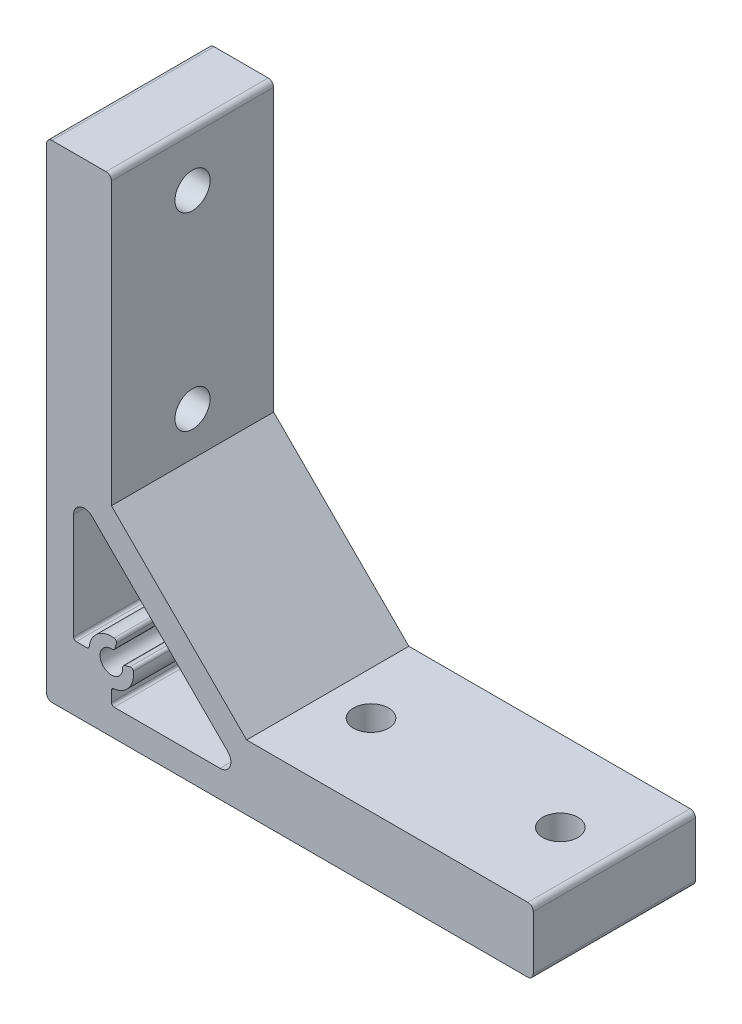
SolidWorks part; units mm, degrees
ref_plane "前视基准面" through (0, 0, 0) normal (0, 0, 1) x (1, 0, 0)
ref_plane "上视基准面" through (0, 0, 0) normal (0, 1, 0) x (1, 0, 0)
ref_plane "右视基准面" through (0, 0, 0) normal (1, 0, 0) x (0, 0, -1)
sketch "草图1" [suppressed] plane through (0, 0, 0) normal (0, 0, 1) x (1, 0, 0)
  line L12 (45, 0) -> (45, 5.7)
  line L13 (45, 5.7) -> (5.7, 5.7)
  line L14 (5.7, 5.7) -> (5.7, 45)
  line L15 (5.7, 45) -> (0, 45)
  line L16 (0, 45) -> (0, 0)
  line L17 (0, 0) -> (45, 0)
extrude "凸台-拉伸1" [suppressed] add sketch "草图1" against normal blind 30
sketch "草图2" [suppressed] plane through (0, 5.7, 0) normal (0, 1, 0) x (1, 0, 0)
  line L0 (45, 30) -> (5.7, 30) construction
  line L1 (0, 30) -> (0, 0) construction
  circle A0 centre (27, 15) radius 3.25
  dimension "D1" = 15
  dimension "D2" = 6.5
  dimension "D3" = 27
extrude "切除-拉伸1" [suppressed] cut sketch "草图2" against normal through all
sketch "草图3" [suppressed] plane through (5.7, 0, 0) normal (1, 0, 0) x (0, 0, -1)
  line L0 (30, 5.7) -> (30, 45) construction
  line L1 (30, 0) -> (0, 0) construction
  circle A0 centre (15, 27) radius 3.25
  dimension "D1" = 15
  dimension "D2" = 6.5
  dimension "D3" = 27
extrude "切除-拉伸2" [suppressed] cut sketch "草图3" against normal through all
sketch "草图4" [suppressed] plane through (0, 0, 0) normal (0, 0, 1) x (1, 0, 0)
  line L12 (45, 0) -> (45, 5.7)
  line L13 (45, 5.7) -> (5.7, 5.7)
  line L14 (5.7, 5.7) -> (5.7, 45)
  line L15 (5.7, 45) -> (0, 45)
  line L16 (0, 45) -> (0, 0)
  line L17 (0, 0) -> (45, 0)
extrude "凸台-拉伸2" [suppressed] add sketch "草图4" against normal blind 70
sketch "草图5" [suppressed] plane through (0, 5.7, 0) normal (0, 1, 0) x (1, 0, 0)
  line L0 (45, 35) -> (12.9539, 35) construction
  line L1 (45, 70) -> (45, 0) construction
  line L2 (0, 70) -> (0, 0) construction
  circle A0 centre (27, 55) radius 3.25
  circle A1 centre (27, 15) radius 3.25
  dimension "D1" = 40
  dimension "D2" = 6.5
  dimension "D3" = 27
extrude "切除-拉伸3" [suppressed] cut sketch "草图5" against normal through all
sketch "草图6" [suppressed] plane through (5.7, 0, 0) normal (1, 0, 0) x (0, 0, -1)
  line L0 (35, 45) -> (35, 17.1363) construction
  line L1 (70, 45) -> (0, 45) construction
  line L2 (70, 0) -> (0, 0) construction
  circle A0 centre (15, 27) radius 3.25
  circle A1 centre (55, 27) radius 3.25
  dimension "D1" = 40
  dimension "D2" = 6.5
  dimension "D3" = 27
extrude "切除-拉伸4" [suppressed] cut sketch "草图6" against normal through all
sketch "草图7" [suppressed] plane through (0, 0, 0) normal (0, 0, 1) x (1, 0, 0)
  line L12 (45, 0) -> (45, 5.7)
  line L13 (45, 5.7) -> (5.7, 5.7)
  line L14 (5.7, 5.7) -> (5.7, 45)
  line L15 (5.7, 45) -> (0, 45)
  line L16 (0, 45) -> (0, 0)
  line L17 (0, 0) -> (45, 0)
extrude "凸台-拉伸3" [suppressed] add sketch "草图7" against normal blind 110
sketch "草图8" [suppressed] plane through (0, 5.7, 0) normal (0, 1, 0) x (1, 0, 0)
  line L0 (45, 55) -> (11.9548, 55) construction
  line L1 (45, 110) -> (45, 0) construction
  line L2 (0, 110) -> (0, 0) construction
  circle A0 centre (27, 95) radius 3.25
  circle A1 centre (27, 55) radius 3.25
  circle A2 centre (27, 15) radius 3.25
  dimension "D1" = 40
  dimension "D2" = 6.5
  dimension "D3" = 27
extrude "切除-拉伸5" [suppressed] cut sketch "草图8" against normal through all
sketch "草图9" [suppressed] plane through (5.7, 0, 0) normal (1, 0, 0) x (0, 0, -1)
  line L0 (55, 45) -> (55, 10.564) construction
  line L1 (110, 45) -> (0, 45) construction
  line L2 (110, 0) -> (0, 0) construction
  circle A0 centre (15, 27) radius 3.25
  circle A1 centre (55, 27) radius 3.25
  circle A2 centre (95, 27) radius 3.25
  dimension "D1" = 40
  dimension "D2" = 6.5
  dimension "D3" = 27
extrude "切除-拉伸6" [suppressed] cut sketch "草图9" against normal through all
sketch "草图10" [suppressed] plane through (0, 0, 0) normal (0, 0, 1) x (1, 0, 0)
  line L20 (15.4436, 12.9227) -> (14.4645, 12.6604)
  line L21 (12.6604, 14.4645) -> (12.9227, 15.4436)
  line L22 (7.8122, 14.1878) -> (5, 17)
  line L23 (5, 17) -> (5, 34)
  line L24 (4, 35) -> (1, 35)
  line L25 (0, 34) -> (0, 1)
  line L26 (1, 0) -> (34, 0)
  line L27 (35, 1) -> (35, 4)
  line L28 (34, 5) -> (17, 5)
  line L29 (17, 5) -> (14.1878, 7.8122)
  arc A28 (14.4645, 12.6604) -> (14.0951, 12.1433) centre (14.5939, 12.1774) ccw
  arc A29 (12.1433, 14.0951) -> (14.0951, 12.1433) centre (12, 12) ccw
  arc A30 (12.1433, 14.0951) -> (12.6604, 14.4645) centre (12.1774, 14.5939) ccw
  arc A31 (12.9227, 15.4436) -> (12.5008, 16.0693) centre (12.4398, 15.573) ccw
  arc A32 (12.5008, 16.0693) -> (8.5825, 14.2651) centre (12, 12) ccw
  arc A33 (7.8122, 14.1878) -> (8.5825, 14.2651) centre (8.1657, 14.5414) ccw
  arc A34 (5, 34) -> (4, 35) centre (4, 34) ccw
  arc A35 (1, 35) -> (0, 34) centre (1, 34) ccw
  arc A36 (0, 1) -> (1, 0) centre (1, 1) ccw
  arc A37 (34, 0) -> (35, 1) centre (34, 1) ccw
  arc A38 (35, 4) -> (34, 5) centre (34, 4) ccw
  arc A39 (14.2651, 8.5825) -> (14.1878, 7.8122) centre (14.5414, 8.1657) ccw
  arc A40 (14.2651, 8.5825) -> (16.0693, 12.5008) centre (12, 12) ccw
  arc A41 (16.0693, 12.5008) -> (15.4436, 12.9227) centre (15.573, 12.4398) ccw
extrude "凸台-拉伸4" [suppressed] add sketch "草图10" against normal blind 30
sketch "草图11" [suppressed] plane through (0, 5, 0) normal (0, 1, 0) x (1, 0, 0)
  line L0 (34, 30) -> (17, 30) construction
  line L1 (0, 30) -> (0, 0) construction
  circle A0 centre (26, 15) radius 3.25
  dimension "D1" = 15
  dimension "D2" = 6.5
  dimension "D3" = 26
extrude "切除-拉伸7" [suppressed] cut sketch "草图11" against normal through all
sketch "草图12" [suppressed] plane through (5, 0, 0) normal (1, 0, 0) x (0, 0, -1)
  line L0 (30, 17) -> (30, 34) construction
  line L1 (30, 0) -> (0, 0) construction
  circle A0 centre (15, 26) radius 3.25
  dimension "D1" = 15
  dimension "D2" = 6.5
  dimension "D3" = 26
extrude "切除-拉伸8" [suppressed] cut sketch "草图12" against normal through all
sketch "草图13" [suppressed] plane through (0, 0, 0) normal (0, 0, 1) x (1, 0, 0)
  line L20 (15.4436, 12.9227) -> (14.4645, 12.6604)
  line L21 (12.6604, 14.4645) -> (12.9227, 15.4436)
  line L22 (7.8122, 14.1878) -> (5, 17)
  line L23 (5, 17) -> (5, 34)
  line L24 (4, 35) -> (1, 35)
  line L25 (0, 34) -> (0, 1)
  line L26 (1, 0) -> (34, 0)
  line L27 (35, 1) -> (35, 4)
  line L28 (34, 5) -> (17, 5)
  line L29 (17, 5) -> (14.1878, 7.8122)
  arc A28 (14.4645, 12.6604) -> (14.0951, 12.1433) centre (14.5939, 12.1774) ccw
  arc A29 (12.1433, 14.0951) -> (14.0951, 12.1433) centre (12, 12) ccw
  arc A30 (12.1433, 14.0951) -> (12.6604, 14.4645) centre (12.1774, 14.5939) ccw
  arc A31 (12.9227, 15.4436) -> (12.5008, 16.0693) centre (12.4398, 15.573) ccw
  arc A32 (12.5008, 16.0693) -> (8.5825, 14.2651) centre (12, 12) ccw
  arc A33 (7.8122, 14.1878) -> (8.5825, 14.2651) centre (8.1657, 14.5414) ccw
  arc A34 (5, 34) -> (4, 35) centre (4, 34) ccw
  arc A35 (1, 35) -> (0, 34) centre (1, 34) ccw
  arc A36 (0, 1) -> (1, 0) centre (1, 1) ccw
  arc A37 (34, 0) -> (35, 1) centre (34, 1) ccw
  arc A38 (35, 4) -> (34, 5) centre (34, 4) ccw
  arc A39 (14.2651, 8.5825) -> (14.1878, 7.8122) centre (14.5414, 8.1657) ccw
  arc A40 (14.2651, 8.5825) -> (16.0693, 12.5008) centre (12, 12) ccw
  arc A41 (16.0693, 12.5008) -> (15.4436, 12.9227) centre (15.573, 12.4398) ccw
extrude "凸台-拉伸5" [suppressed] add sketch "草图13" against normal blind 70
sketch "草图14" [suppressed] plane through (0, 5, 0) normal (0, 1, 0) x (1, 0, 0)
  line L0 (35, 35) -> (20.3355, 35) construction
  line L1 (35, 70) -> (35, 0) construction
  line L2 (0, 70) -> (0, 0) construction
  circle A0 centre (26, 55) radius 3.25
  circle A1 centre (26, 15) radius 3.25
  dimension "D1" = 40
  dimension "D2" = 6.5
  dimension "D3" = 26
extrude "切除-拉伸9" [suppressed] cut sketch "草图14" against normal through all
sketch "草图15" [suppressed] plane through (5, 0, 0) normal (1, 0, 0) x (0, 0, -1)
  line L0 (35, 35) -> (35, 18.8877) construction
  line L1 (70, 35) -> (0, 35) construction
  line L2 (70, 0) -> (0, 0) construction
  circle A0 centre (15, 26) radius 3.25
  circle A1 centre (55, 26) radius 3.25
  dimension "D1" = 6.5
  dimension "D2" = 40
  dimension "D3" = 26
extrude "切除-拉伸10" [suppressed] cut sketch "草图15" against normal through all
sketch "草图16" [suppressed] plane through (0, 0, 0) normal (0, 0, 1) x (1, 0, 0)
  line L20 (15.4436, 12.9227) -> (14.4645, 12.6604)
  line L21 (12.6604, 14.4645) -> (12.9227, 15.4436)
  line L22 (7.8122, 14.1878) -> (5, 17)
  line L23 (5, 17) -> (5, 34)
  line L24 (4, 35) -> (1, 35)
  line L25 (0, 34) -> (0, 1)
  line L26 (1, 0) -> (34, 0)
  line L27 (35, 1) -> (35, 4)
  line L28 (34, 5) -> (17, 5)
  line L29 (17, 5) -> (14.1878, 7.8122)
  arc A28 (14.4645, 12.6604) -> (14.0951, 12.1433) centre (14.5939, 12.1774) ccw
  arc A29 (12.1433, 14.0951) -> (14.0951, 12.1433) centre (12, 12) ccw
  arc A30 (12.1433, 14.0951) -> (12.6604, 14.4645) centre (12.1774, 14.5939) ccw
  arc A31 (12.9227, 15.4436) -> (12.5008, 16.0693) centre (12.4398, 15.573) ccw
  arc A32 (12.5008, 16.0693) -> (8.5825, 14.2651) centre (12, 12) ccw
  arc A33 (7.8122, 14.1878) -> (8.5825, 14.2651) centre (8.1657, 14.5414) ccw
  arc A34 (5, 34) -> (4, 35) centre (4, 34) ccw
  arc A35 (1, 35) -> (0, 34) centre (1, 34) ccw
  arc A36 (0, 1) -> (1, 0) centre (1, 1) ccw
  arc A37 (34, 0) -> (35, 1) centre (34, 1) ccw
  arc A38 (35, 4) -> (34, 5) centre (34, 4) ccw
  arc A39 (14.2651, 8.5825) -> (14.1878, 7.8122) centre (14.5414, 8.1657) ccw
  arc A40 (14.2651, 8.5825) -> (16.0693, 12.5008) centre (12, 12) ccw
  arc A41 (16.0693, 12.5008) -> (15.4436, 12.9227) centre (15.573, 12.4398) ccw
extrude "凸台-拉伸6" [suppressed] add sketch "草图16" against normal blind 110
sketch "草图17" [suppressed] plane through (0, 5, 0) normal (0, 1, 0) x (1, 0, 0)
  line L0 (35, 55) -> (49.4328, 55) construction
  line L1 (35, 110) -> (35, 0) construction
  line L2 (0, 110) -> (0, 0) construction
  circle A0 centre (26, 95) radius 3.25
  circle A1 centre (26, 55) radius 3.25
  circle A2 centre (26, 15) radius 3.25
  dimension "D1" = 40
  dimension "D2" = 6.5
  dimension "D3" = 26
extrude "切除-拉伸11" [suppressed] cut sketch "草图17" against normal through all
sketch "草图18" [suppressed] plane through (5, 0, 0) normal (1, 0, 0) x (0, 0, -1)
  line L0 (55, 35) -> (55, 20.0249) construction
  line L1 (110, 35) -> (0, 35) construction
  line L2 (110, 0) -> (0, 0) construction
  circle A0 centre (15, 26) radius 3.25
  circle A1 centre (55, 26) radius 3.25
  circle A2 centre (95, 26) radius 3.25
  dimension "D1" = 40
  dimension "D2" = 6.5
  dimension "D3" = 26
extrude "切除-拉伸12" [suppressed] cut sketch "草图18" against normal through all
sketch "草图19" [suppressed] plane through (0, 0, 0) normal (0, 0, 1) x (1, 0, 0)
  line L20 (9.6443, 15.3557) -> (9, 16.4873)
  line L21 (9, 16.4873) -> (9, 54)
  line L22 (8, 55) -> (1, 55)
  line L23 (0, 54) -> (0, 1)
  line L24 (1, 0) -> (54, 0)
  line L25 (55, 1) -> (55, 8)
  line L26 (54, 9) -> (16.4873, 9)
  line L27 (16.4873, 9) -> (15.3557, 9.6443)
  line L28 (15.4436, 12.9227) -> (14.4645, 12.6604)
  line L29 (12.6604, 14.4645) -> (12.9227, 15.4436)
  arc A24 (12.9227, 15.4436) -> (12.5008, 16.0693) centre (12.4398, 15.573) ccw
  arc A25 (12.5008, 16.0693) -> (9.6443, 15.3557) centre (12, 12) ccw
  arc A26 (9, 54) -> (8, 55) centre (8, 54) ccw
  arc A27 (1, 55) -> (0, 54) centre (1, 54) ccw
  arc A28 (0, 1) -> (1, 0) centre (1, 1) ccw
  arc A29 (54, 0) -> (55, 1) centre (54, 1) ccw
  arc A30 (55, 8) -> (54, 9) centre (54, 8) ccw
  arc A31 (15.3557, 9.6443) -> (16.0693, 12.5008) centre (12, 12) ccw
  arc A32 (16.0693, 12.5008) -> (15.4436, 12.9227) centre (15.573, 12.4398) ccw
  arc A33 (14.4645, 12.6604) -> (14.0951, 12.1433) centre (14.5939, 12.1774) ccw
  arc A34 (12.1433, 14.0951) -> (14.0951, 12.1433) centre (12, 12) ccw
  arc A35 (12.1433, 14.0951) -> (12.6604, 14.4645) centre (12.1774, 14.5939) ccw
extrude "凸台-拉伸7" [suppressed] add sketch "草图19" against normal blind 30
sketch "草图20" [suppressed] plane through (0, 9, 0) normal (0, 1, 0) x (1, 0, 0)
  line L0 (54, 30) -> (16.4873, 30) construction
  line L1 (0, 30) -> (0, 0) construction
  circle A0 centre (25, 15) radius 3.25
  circle A1 centre (45, 15) radius 3.25
  dimension "D1" = 15
  dimension "D2" = 6.5
  dimension "D3" = 25
  dimension "D4" = 45
extrude "切除-拉伸13" [suppressed] cut sketch "草图20" against normal through all
sketch "草图21" [suppressed] plane through (9, 0, 0) normal (1, 0, 0) x (0, 0, -1)
  line L0 (0, 16.4873) -> (0, 54) construction
  line L1 (30, 0) -> (0, 0) construction
  circle A0 centre (15, 45) radius 3.25
  circle A1 centre (15, 25) radius 3.25
  dimension "D1" = 15
  dimension "D2" = 6.5
  dimension "D3" = 25
  dimension "D4" = 45
extrude "切除-拉伸14" [suppressed] cut sketch "草图21" against normal through all
sketch "草图22" [suppressed] plane through (0, 0, 0) normal (0, 0, 1) x (1, 0, 0)
  line L20 (9.6443, 15.3557) -> (9, 16.4873)
  line L21 (9, 16.4873) -> (9, 54)
  line L22 (8, 55) -> (1, 55)
  line L23 (0, 54) -> (0, 1)
  line L24 (1, 0) -> (54, 0)
  line L25 (55, 1) -> (55, 8)
  line L26 (54, 9) -> (16.4873, 9)
  line L27 (16.4873, 9) -> (15.3557, 9.6443)
  line L28 (15.4436, 12.9227) -> (14.4645, 12.6604)
  line L29 (12.6604, 14.4645) -> (12.9227, 15.4436)
  arc A24 (12.9227, 15.4436) -> (12.5008, 16.0693) centre (12.4398, 15.573) ccw
  arc A25 (12.5008, 16.0693) -> (9.6443, 15.3557) centre (12, 12) ccw
  arc A26 (9, 54) -> (8, 55) centre (8, 54) ccw
  arc A27 (1, 55) -> (0, 54) centre (1, 54) ccw
  arc A28 (0, 1) -> (1, 0) centre (1, 1) ccw
  arc A29 (54, 0) -> (55, 1) centre (54, 1) ccw
  arc A30 (55, 8) -> (54, 9) centre (54, 8) ccw
  arc A31 (15.3557, 9.6443) -> (16.0693, 12.5008) centre (12, 12) ccw
  arc A32 (16.0693, 12.5008) -> (15.4436, 12.9227) centre (15.573, 12.4398) ccw
  arc A33 (14.4645, 12.6604) -> (14.0951, 12.1433) centre (14.5939, 12.1774) ccw
  arc A34 (12.1433, 14.0951) -> (14.0951, 12.1433) centre (12, 12) ccw
  arc A35 (12.1433, 14.0951) -> (12.6604, 14.4645) centre (12.1774, 14.5939) ccw
extrude "凸台-拉伸8" [suppressed] add sketch "草图22" against normal blind 70
sketch "草图23" [suppressed] plane through (0, 9, 0) normal (0, 1, 0) x (1, 0, 0)
  line L0 (55, 35) -> (23.7194, 35) construction
  line L1 (55, 70) -> (55, 0) construction
  line L2 (0, 70) -> (0, 0) construction
  circle A0 centre (25, 55) radius 3.25
  circle A1 centre (45, 55) radius 3.25
  circle A2 centre (45, 15) radius 3.25
  circle A3 centre (25, 15) radius 3.25
  dimension "D1" = 40
  dimension "D2" = 6.5
  dimension "D3" = 25
  dimension "D4" = 45
extrude "切除-拉伸15" [suppressed] cut sketch "草图23" against normal through all
sketch "草图24" [suppressed] plane through (9, 0, 0) normal (1, 0, 0) x (0, 0, -1)
  line L0 (35, 55) -> (35, 23.7126) construction
  line L1 (70, 55) -> (0, 55) construction
  line L2 (70, 0) -> (0, 0) construction
  circle A0 centre (15, 45) radius 3.25
  circle A1 centre (15, 25) radius 3.25
  circle A2 centre (55, 25) radius 3.25
  circle A3 centre (55, 45) radius 3.25
  dimension "D1" = 40
  dimension "D2" = 6.5
  dimension "D3" = 25
  dimension "D4" = 45
extrude "切除-拉伸16" [suppressed] cut sketch "草图24" against normal through all
sketch "草图25" [suppressed] plane through (0, 0, 0) normal (0, 0, 1) x (1, 0, 0)
  line L20 (9.6443, 15.3557) -> (9, 16.4873)
  line L21 (9, 16.4873) -> (9, 54)
  line L22 (8, 55) -> (1, 55)
  line L23 (0, 54) -> (0, 1)
  line L24 (1, 0) -> (54, 0)
  line L25 (55, 1) -> (55, 8)
  line L26 (54, 9) -> (16.4873, 9)
  line L27 (16.4873, 9) -> (15.3557, 9.6443)
  line L28 (15.4436, 12.9227) -> (14.4645, 12.6604)
  line L29 (12.6604, 14.4645) -> (12.9227, 15.4436)
  arc A24 (12.9227, 15.4436) -> (12.5008, 16.0693) centre (12.4398, 15.573) ccw
  arc A25 (12.5008, 16.0693) -> (9.6443, 15.3557) centre (12, 12) ccw
  arc A26 (9, 54) -> (8, 55) centre (8, 54) ccw
  arc A27 (1, 55) -> (0, 54) centre (1, 54) ccw
  arc A28 (0, 1) -> (1, 0) centre (1, 1) ccw
  arc A29 (54, 0) -> (55, 1) centre (54, 1) ccw
  arc A30 (55, 8) -> (54, 9) centre (54, 8) ccw
  arc A31 (15.3557, 9.6443) -> (16.0693, 12.5008) centre (12, 12) ccw
  arc A32 (16.0693, 12.5008) -> (15.4436, 12.9227) centre (15.573, 12.4398) ccw
  arc A33 (14.4645, 12.6604) -> (14.0951, 12.1433) centre (14.5939, 12.1774) ccw
  arc A34 (12.1433, 14.0951) -> (14.0951, 12.1433) centre (12, 12) ccw
  arc A35 (12.1433, 14.0951) -> (12.6604, 14.4645) centre (12.1774, 14.5939) ccw
extrude "凸台-拉伸9" [suppressed] add sketch "草图25" against normal blind 110
sketch "草图26" [suppressed] plane through (0, 9, 0) normal (0, 1, 0) x (1, 0, 0)
  line L0 (55, 55) -> (73.0069, 55) construction
  line L1 (55, 110) -> (55, 0) construction
  line L2 (0, 110) -> (0, 0) construction
  circle A0 centre (25, 95) radius 3.25
  circle A1 centre (45, 95) radius 3.25
  circle A2 centre (25, 55) radius 3.25
  circle A3 centre (45, 55) radius 3.25
  circle A4 centre (45, 15) radius 3.25
  circle A5 centre (25, 15) radius 3.25
  dimension "D1" = 40
  dimension "D2" = 6.5
  dimension "D3" = 25
  dimension "D4" = 45
extrude "切除-拉伸17" [suppressed] cut sketch "草图26" against normal through all
sketch "草图27" [suppressed] plane through (9, 0, 0) normal (1, 0, 0) x (0, 0, -1)
  line L0 (55, 55) -> (55, 66.5215) construction
  line L1 (110, 55) -> (0, 55) construction
  line L2 (110, 0) -> (0, 0) construction
  circle A0 centre (15, 45) radius 3.25
  circle A1 centre (15, 25) radius 3.25
  circle A2 centre (55, 45) radius 3.25
  circle A3 centre (55, 25) radius 3.25
  circle A4 centre (95, 25) radius 3.25
  circle A5 centre (95, 45) radius 3.25
  dimension "D1" = 40
  dimension "D2" = 6.5
  dimension "D3" = 25
  dimension "D4" = 45
extrude "切除-拉伸18" [suppressed] cut sketch "草图27" against normal through all
sketch "草图28" [suppressed] plane through (0, 0, 0) normal (0, 0, 1) x (1, 0, 0)
  line L14 (1, 0) -> (49, 0)
  line L15 (50, 1) -> (50, 8)
  line L16 (49, 9) -> (30, 9)
  line L17 (30, 9) -> (9, 30)
  line L18 (9, 30) -> (9, 49)
  line L19 (8, 50) -> (1, 50)
  line L20 (0, 49) -> (0, 1)
  line L28 (12, 7.4273) -> (12, 5.5)
  line L29 (14.4645, 12.6604) -> (15.4436, 12.9227)
  line L30 (12.9227, 15.4436) -> (12.6604, 14.4645)
  line L31 (5.5, 12) -> (7.4273, 12)
  line L32 (5, 24.2218) -> (5, 12.5)
  line L33 (25.636, 8.4142) -> (8.4142, 25.636)
  line L34 (12.5, 5) -> (24.2218, 5)
  arc A10 (49, 0) -> (50, 1) centre (49, 1) ccw
  arc A11 (50, 8) -> (49, 9) centre (49, 8) ccw
  arc A12 (9, 49) -> (8, 50) centre (8, 49) ccw
  arc A13 (1, 50) -> (0, 49) centre (1, 49) ccw
  arc A14 (0, 1) -> (1, 0) centre (1, 1) ccw
  arc A36 (12.4457, 7.9243) -> (12, 7.4273) centre (12.5, 7.4273) ccw
  arc A37 (12.4457, 7.9243) -> (16.0693, 12.5008) centre (12, 12) ccw
  arc A38 (16.0693, 12.5008) -> (15.4436, 12.9227) centre (15.573, 12.4398) ccw
  arc A39 (14.4645, 12.6604) -> (14.0951, 12.1433) centre (14.5939, 12.1774) ccw
  arc A40 (12.1433, 14.0951) -> (14.0951, 12.1433) centre (12, 12) ccw
  arc A41 (12.1433, 14.0951) -> (12.6604, 14.4645) centre (12.1774, 14.5939) ccw
  arc A42 (12.9227, 15.4436) -> (12.5008, 16.0693) centre (12.4398, 15.573) ccw
  arc A43 (12.5008, 16.0693) -> (7.9243, 12.4457) centre (12, 12) ccw
  arc A44 (7.4273, 12) -> (7.9243, 12.4457) centre (7.4273, 12.5) ccw
  arc A45 (5, 12.5) -> (5.5, 12) centre (5.5, 12.5) ccw
  arc A46 (8.4142, 25.636) -> (5, 24.2218) centre (7, 24.2218) ccw
  arc A47 (24.2218, 5) -> (25.636, 8.4142) centre (24.2218, 7) ccw
  arc A48 (12, 5.5) -> (12.5, 5) centre (12.5, 5.5) ccw
extrude "凸台-拉伸10" [suppressed] add sketch "草图28" against normal blind 30
sketch "草图29" [suppressed] plane through (0, 9, 0) normal (0, 1, 0) x (1, 0, 0)
  line L0 (49, 30) -> (30, 30) construction
  line L1 (0, 30) -> (0, 0) construction
  circle A0 centre (40, 15) radius 3.25
  point P2 (39.5, 30)
  dimension "D1" = 15
  dimension "D2" = 6.5
  dimension "D3" = 40
extrude "切除-拉伸19" [suppressed] cut sketch "草图29" against normal through all
sketch "草图30" [suppressed] plane through (9, 0, 0) normal (1, 0, 0) x (0, 0, -1)
  line L0 (0, 30) -> (0, 49) construction
  line L1 (30, 0) -> (0, 0) construction
  circle A0 centre (15, 40) radius 3.25
  dimension "D1" = 15
  dimension "D2" = 6.5
  dimension "D3" = 40
extrude "切除-拉伸20" [suppressed] cut sketch "草图30" against normal through all
sketch "草图31" [suppressed] plane through (0, 0, 0) normal (0, 0, 1) x (1, 0, 0)
  line L14 (1, 0) -> (49, 0)
  line L15 (50, 1) -> (50, 8)
  line L16 (49, 9) -> (30, 9)
  line L17 (30, 9) -> (9, 30)
  line L18 (9, 30) -> (9, 49)
  line L19 (8, 50) -> (1, 50)
  line L20 (0, 49) -> (0, 1)
  line L28 (12, 7.4273) -> (12, 5.5)
  line L29 (14.4645, 12.6604) -> (15.4436, 12.9227)
  line L30 (12.9227, 15.4436) -> (12.6604, 14.4645)
  line L31 (5.5, 12) -> (7.4273, 12)
  line L32 (5, 24.2218) -> (5, 12.5)
  line L33 (25.636, 8.4142) -> (8.4142, 25.636)
  line L34 (12.5, 5) -> (24.2218, 5)
  arc A10 (49, 0) -> (50, 1) centre (49, 1) ccw
  arc A11 (50, 8) -> (49, 9) centre (49, 8) ccw
  arc A12 (9, 49) -> (8, 50) centre (8, 49) ccw
  arc A13 (1, 50) -> (0, 49) centre (1, 49) ccw
  arc A14 (0, 1) -> (1, 0) centre (1, 1) ccw
  arc A36 (12.4457, 7.9243) -> (12, 7.4273) centre (12.5, 7.4273) ccw
  arc A37 (12.4457, 7.9243) -> (16.0693, 12.5008) centre (12, 12) ccw
  arc A38 (16.0693, 12.5008) -> (15.4436, 12.9227) centre (15.573, 12.4398) ccw
  arc A39 (14.4645, 12.6604) -> (14.0951, 12.1433) centre (14.5939, 12.1774) ccw
  arc A40 (12.1433, 14.0951) -> (14.0951, 12.1433) centre (12, 12) ccw
  arc A41 (12.1433, 14.0951) -> (12.6604, 14.4645) centre (12.1774, 14.5939) ccw
  arc A42 (12.9227, 15.4436) -> (12.5008, 16.0693) centre (12.4398, 15.573) ccw
  arc A43 (12.5008, 16.0693) -> (7.9243, 12.4457) centre (12, 12) ccw
  arc A44 (7.4273, 12) -> (7.9243, 12.4457) centre (7.4273, 12.5) ccw
  arc A45 (5, 12.5) -> (5.5, 12) centre (5.5, 12.5) ccw
  arc A46 (8.4142, 25.636) -> (5, 24.2218) centre (7, 24.2218) ccw
  arc A47 (24.2218, 5) -> (25.636, 8.4142) centre (24.2218, 7) ccw
  arc A48 (12, 5.5) -> (12.5, 5) centre (12.5, 5.5) ccw
extrude "凸台-拉伸11" [suppressed] add sketch "草图31" against normal blind 70
sketch "草图32" [suppressed] plane through (0, 9, 0) normal (0, 1, 0) x (1, 0, 0)
  line L0 (50, 35) -> (32.9393, 35) construction
  line L1 (50, 70) -> (50, 0) construction
  line L2 (0, 70) -> (0, 0) construction
  circle A0 centre (40, 55) radius 3.25
  circle A1 centre (40, 15) radius 3.25
  dimension "D1" = 40
  dimension "D2" = 6.5
  dimension "D3" = 40
extrude "切除-拉伸21" [suppressed] cut sketch "草图32" against normal through all
sketch "草图33" [suppressed] plane through (9, 0, 0) normal (1, 0, 0) x (0, 0, -1)
  line L0 (35, 50) -> (35, 33.399) construction
  line L1 (70, 50) -> (0, 50) construction
  line L2 (70, 0) -> (0, 0) construction
  circle A0 centre (15, 40) radius 3.25
  circle A1 centre (55, 40) radius 3.25
  dimension "D1" = 40
  dimension "D2" = 6.5
  dimension "D3" = 40
extrude "切除-拉伸22" [suppressed] cut sketch "草图33" against normal through all
sketch "草图34" [suppressed] plane through (0, 0, 0) normal (0, 0, 1) x (1, 0, 0)
  line L14 (1, 0) -> (49, 0)
  line L15 (50, 1) -> (50, 8)
  line L16 (49, 9) -> (30, 9)
  line L17 (30, 9) -> (9, 30)
  line L18 (9, 30) -> (9, 49)
  line L19 (8, 50) -> (1, 50)
  line L20 (0, 49) -> (0, 1)
  line L28 (12, 7.4273) -> (12, 5.5)
  line L29 (14.4645, 12.6604) -> (15.4436, 12.9227)
  line L30 (12.9227, 15.4436) -> (12.6604, 14.4645)
  line L31 (5.5, 12) -> (7.4273, 12)
  line L32 (5, 24.2218) -> (5, 12.5)
  line L33 (25.636, 8.4142) -> (8.4142, 25.636)
  line L34 (12.5, 5) -> (24.2218, 5)
  arc A10 (49, 0) -> (50, 1) centre (49, 1) ccw
  arc A11 (50, 8) -> (49, 9) centre (49, 8) ccw
  arc A12 (9, 49) -> (8, 50) centre (8, 49) ccw
  arc A13 (1, 50) -> (0, 49) centre (1, 49) ccw
  arc A14 (0, 1) -> (1, 0) centre (1, 1) ccw
  arc A36 (12.4457, 7.9243) -> (12, 7.4273) centre (12.5, 7.4273) ccw
  arc A37 (12.4457, 7.9243) -> (16.0693, 12.5008) centre (12, 12) ccw
  arc A38 (16.0693, 12.5008) -> (15.4436, 12.9227) centre (15.573, 12.4398) ccw
  arc A39 (14.4645, 12.6604) -> (14.0951, 12.1433) centre (14.5939, 12.1774) ccw
  arc A40 (12.1433, 14.0951) -> (14.0951, 12.1433) centre (12, 12) ccw
  arc A41 (12.1433, 14.0951) -> (12.6604, 14.4645) centre (12.1774, 14.5939) ccw
  arc A42 (12.9227, 15.4436) -> (12.5008, 16.0693) centre (12.4398, 15.573) ccw
  arc A43 (12.5008, 16.0693) -> (7.9243, 12.4457) centre (12, 12) ccw
  arc A44 (7.4273, 12) -> (7.9243, 12.4457) centre (7.4273, 12.5) ccw
  arc A45 (5, 12.5) -> (5.5, 12) centre (5.5, 12.5) ccw
  arc A46 (8.4142, 25.636) -> (5, 24.2218) centre (7, 24.2218) ccw
  arc A47 (24.2218, 5) -> (25.636, 8.4142) centre (24.2218, 7) ccw
  arc A48 (12, 5.5) -> (12.5, 5) centre (12.5, 5.5) ccw
extrude "凸台-拉伸12" [suppressed] add sketch "草图34" against normal blind 110
sketch "草图35" [suppressed] plane through (0, 9, 0) normal (0, 1, 0) x (1, 0, 0)
  line L0 (50, 55) -> (65.5472, 55) construction
  line L1 (50, 110) -> (50, 0) construction
  line L2 (0, 110) -> (0, 0) construction
  circle A0 centre (40, 95) radius 3.25
  circle A1 centre (40, 55) radius 3.25
  circle A2 centre (40, 15) radius 3.25
  dimension "D1" = 40
  dimension "D2" = 6.5
  dimension "D3" = 40
extrude "切除-拉伸23" [suppressed] cut sketch "草图35" against normal through all
sketch "草图36" [suppressed] plane through (9, 0, 0) normal (1, 0, 0) x (0, 0, -1)
  line L0 (55, 50) -> (55, 32.0009) construction
  line L1 (110, 50) -> (0, 50) construction
  line L2 (110, 0) -> (0, 0) construction
  circle A0 centre (15, 40) radius 3.25
  circle A1 centre (55, 40) radius 3.25
  circle A2 centre (95, 40) radius 3.25
  dimension "D1" = 40
  dimension "D2" = 6.5
  dimension "D3" = 40
extrude "切除-拉伸24" [suppressed] cut sketch "草图36" against normal through all
sketch "草图37" [suppressed] plane through (0, 0, 0) normal (0, 0, 1) x (1, 0, 0)
  line L14 (1, 0) -> (59, 0)
  line L15 (60, 1) -> (60, 8)
  line L16 (59, 9) -> (40, 9)
  line L17 (40, 9) -> (9, 40)
  line L18 (9, 40) -> (9, 59)
  line L19 (8, 60) -> (1, 60)
  line L20 (0, 59) -> (0, 1)
  line L28 (5.5, 12) -> (7.4273, 12)
  line L29 (5, 36.636) -> (5, 12.5)
  line L30 (37.3431, 6.7071) -> (6.7071, 37.3431)
  line L31 (12.5, 5) -> (36.636, 5)
  line L32 (12, 7.4273) -> (12, 5.5)
  line L33 (14.4645, 12.6604) -> (15.4436, 12.9227)
  line L34 (12.9227, 15.4436) -> (12.6604, 14.4645)
  arc A10 (59, 0) -> (60, 1) centre (59, 1) ccw
  arc A11 (60, 8) -> (59, 9) centre (59, 8) ccw
  arc A12 (9, 59) -> (8, 60) centre (8, 59) ccw
  arc A13 (1, 60) -> (0, 59) centre (1, 59) ccw
  arc A14 (0, 1) -> (1, 0) centre (1, 1) ccw
  arc A36 (5, 12.5) -> (5.5, 12) centre (5.5, 12.5) ccw
  arc A37 (6.7071, 37.3431) -> (5, 36.636) centre (6, 36.636) ccw
  arc A38 (36.636, 5) -> (37.3431, 6.7071) centre (36.636, 6) ccw
  arc A39 (12, 5.5) -> (12.5, 5) centre (12.5, 5.5) ccw
  arc A40 (12.4457, 7.9243) -> (12, 7.4273) centre (12.5, 7.4273) ccw
  arc A41 (12.4457, 7.9243) -> (16.0693, 12.5008) centre (12, 12) ccw
  arc A42 (16.0693, 12.5008) -> (15.4436, 12.9227) centre (15.573, 12.4398) ccw
  arc A43 (14.4645, 12.6604) -> (14.0951, 12.1433) centre (14.5939, 12.1774) ccw
  arc A44 (12.1433, 14.0951) -> (14.0951, 12.1433) centre (12, 12) ccw
  arc A45 (12.1433, 14.0951) -> (12.6604, 14.4645) centre (12.1774, 14.5939) ccw
  arc A46 (12.9227, 15.4436) -> (12.5008, 16.0693) centre (12.4398, 15.573) ccw
  arc A47 (12.5008, 16.0693) -> (7.9243, 12.4457) centre (12, 12) ccw
  arc A48 (7.4273, 12) -> (7.9243, 12.4457) centre (7.4273, 12.5) ccw
extrude "凸台-拉伸13" [suppressed] add sketch "草图37" against normal blind 30
sketch "草图38" [suppressed] plane through (0, 9, 0) normal (0, 1, 0) x (1, 0, 0)
  line L0 (59, 30) -> (40, 30) construction
  line L1 (0, 30) -> (0, 0) construction
  circle A0 centre (50, 15) radius 3.25
  dimension "D1" = 15
  dimension "D2" = 6.5
  dimension "D3" = 50
extrude "切除-拉伸25" [suppressed] cut sketch "草图38" against normal through all
sketch "草图39" [suppressed] plane through (9, 0, 0) normal (1, 0, 0) x (0, 0, -1)
  line L0 (0, 40) -> (0, 59) construction
  line L1 (30, 0) -> (0, 0) construction
  circle A0 centre (15, 50) radius 3.25
  dimension "D1" = 15
  dimension "D2" = 6.5
  dimension "D3" = 50
extrude "切除-拉伸26" [suppressed] cut sketch "草图39" against normal through all
sketch "草图40" [suppressed] plane through (0, 0, 0) normal (0, 0, 1) x (1, 0, 0)
  line L14 (1, 0) -> (59, 0)
  line L15 (60, 1) -> (60, 8)
  line L16 (59, 9) -> (40, 9)
  line L17 (40, 9) -> (9, 40)
  line L18 (9, 40) -> (9, 59)
  line L19 (8, 60) -> (1, 60)
  line L20 (0, 59) -> (0, 1)
  line L28 (5.5, 12) -> (7.4273, 12)
  line L29 (5, 36.636) -> (5, 12.5)
  line L30 (37.3431, 6.7071) -> (6.7071, 37.3431)
  line L31 (12.5, 5) -> (36.636, 5)
  line L32 (12, 7.4273) -> (12, 5.5)
  line L33 (14.4645, 12.6604) -> (15.4436, 12.9227)
  line L34 (12.9227, 15.4436) -> (12.6604, 14.4645)
  arc A10 (59, 0) -> (60, 1) centre (59, 1) ccw
  arc A11 (60, 8) -> (59, 9) centre (59, 8) ccw
  arc A12 (9, 59) -> (8, 60) centre (8, 59) ccw
  arc A13 (1, 60) -> (0, 59) centre (1, 59) ccw
  arc A14 (0, 1) -> (1, 0) centre (1, 1) ccw
  arc A36 (5, 12.5) -> (5.5, 12) centre (5.5, 12.5) ccw
  arc A37 (6.7071, 37.3431) -> (5, 36.636) centre (6, 36.636) ccw
  arc A38 (36.636, 5) -> (37.3431, 6.7071) centre (36.636, 6) ccw
  arc A39 (12, 5.5) -> (12.5, 5) centre (12.5, 5.5) ccw
  arc A40 (12.4457, 7.9243) -> (12, 7.4273) centre (12.5, 7.4273) ccw
  arc A41 (12.4457, 7.9243) -> (16.0693, 12.5008) centre (12, 12) ccw
  arc A42 (16.0693, 12.5008) -> (15.4436, 12.9227) centre (15.573, 12.4398) ccw
  arc A43 (14.4645, 12.6604) -> (14.0951, 12.1433) centre (14.5939, 12.1774) ccw
  arc A44 (12.1433, 14.0951) -> (14.0951, 12.1433) centre (12, 12) ccw
  arc A45 (12.1433, 14.0951) -> (12.6604, 14.4645) centre (12.1774, 14.5939) ccw
  arc A46 (12.9227, 15.4436) -> (12.5008, 16.0693) centre (12.4398, 15.573) ccw
  arc A47 (12.5008, 16.0693) -> (7.9243, 12.4457) centre (12, 12) ccw
  arc A48 (7.4273, 12) -> (7.9243, 12.4457) centre (7.4273, 12.5) ccw
extrude "凸台-拉伸14" [suppressed] add sketch "草图40" against normal blind 70
sketch "草图41" [suppressed] plane through (0, 9, 0) normal (0, 1, 0) x (1, 0, 0)
  line L0 (60, 35) -> (43.7232, 35) construction
  line L1 (60, 70) -> (60, 0) construction
  line L2 (0, 70) -> (0, 0) construction
  circle A0 centre (50, 55) radius 3.25
  circle A1 centre (50, 15) radius 3.25
  dimension "D1" = 40
  dimension "D2" = 6.5
  dimension "D3" = 50
extrude "切除-拉伸27" [suppressed] cut sketch "草图41" against normal through all
sketch "草图42" [suppressed] plane through (9, 0, 0) normal (1, 0, 0) x (0, 0, -1)
  line L0 (35, 60) -> (35, 41.5843) construction
  line L1 (70, 60) -> (0, 60) construction
  line L2 (70, 0) -> (0, 0) construction
  circle A0 centre (15, 50) radius 3.25
  circle A1 centre (55, 50) radius 3.25
  dimension "D1" = 40
  dimension "D2" = 6.5
  dimension "D3" = 50
extrude "切除-拉伸28" [suppressed] cut sketch "草图42" against normal through all
sketch "草图43" [suppressed] plane through (0, 0, 0) normal (0, 0, 1) x (1, 0, 0)
  line L14 (1, 0) -> (59, 0)
  line L15 (60, 1) -> (60, 8)
  line L16 (59, 9) -> (40, 9)
  line L17 (40, 9) -> (9, 40)
  line L18 (9, 40) -> (9, 59)
  line L19 (8, 60) -> (1, 60)
  line L20 (0, 59) -> (0, 1)
  line L28 (5.5, 12) -> (7.4273, 12)
  line L29 (5, 36.636) -> (5, 12.5)
  line L30 (37.3431, 6.7071) -> (6.7071, 37.3431)
  line L31 (12.5, 5) -> (36.636, 5)
  line L32 (12, 7.4273) -> (12, 5.5)
  line L33 (14.4645, 12.6604) -> (15.4436, 12.9227)
  line L34 (12.9227, 15.4436) -> (12.6604, 14.4645)
  arc A10 (59, 0) -> (60, 1) centre (59, 1) ccw
  arc A11 (60, 8) -> (59, 9) centre (59, 8) ccw
  arc A12 (9, 59) -> (8, 60) centre (8, 59) ccw
  arc A13 (1, 60) -> (0, 59) centre (1, 59) ccw
  arc A14 (0, 1) -> (1, 0) centre (1, 1) ccw
  arc A36 (5, 12.5) -> (5.5, 12) centre (5.5, 12.5) ccw
  arc A37 (6.7071, 37.3431) -> (5, 36.636) centre (6, 36.636) ccw
  arc A38 (36.636, 5) -> (37.3431, 6.7071) centre (36.636, 6) ccw
  arc A39 (12, 5.5) -> (12.5, 5) centre (12.5, 5.5) ccw
  arc A40 (12.4457, 7.9243) -> (12, 7.4273) centre (12.5, 7.4273) ccw
  arc A41 (12.4457, 7.9243) -> (16.0693, 12.5008) centre (12, 12) ccw
  arc A42 (16.0693, 12.5008) -> (15.4436, 12.9227) centre (15.573, 12.4398) ccw
  arc A43 (14.4645, 12.6604) -> (14.0951, 12.1433) centre (14.5939, 12.1774) ccw
  arc A44 (12.1433, 14.0951) -> (14.0951, 12.1433) centre (12, 12) ccw
  arc A45 (12.1433, 14.0951) -> (12.6604, 14.4645) centre (12.1774, 14.5939) ccw
  arc A46 (12.9227, 15.4436) -> (12.5008, 16.0693) centre (12.4398, 15.573) ccw
  arc A47 (12.5008, 16.0693) -> (7.9243, 12.4457) centre (12, 12) ccw
  arc A48 (7.4273, 12) -> (7.9243, 12.4457) centre (7.4273, 12.5) ccw
extrude "凸台-拉伸15" [suppressed] add sketch "草图43" against normal blind 110
sketch "草图44" [suppressed] plane through (0, 9, 0) normal (0, 1, 0) x (1, 0, 0)
  line L0 (60, 55) -> (79.0791, 55) construction
  line L1 (60, 110) -> (60, 0) construction
  line L2 (0, 110) -> (0, 0) construction
  circle A0 centre (50, 95) radius 3.25
  circle A1 centre (50, 55) radius 3.25
  circle A2 centre (50, 15) radius 3.25
  dimension "D1" = 40
  dimension "D2" = 6.5
  dimension "D3" = 50
extrude "切除-拉伸29" [suppressed] cut sketch "草图44" against normal through all
sketch "草图45" [suppressed] plane through (9, 0, 0) normal (1, 0, 0) x (0, 0, -1)
  line L0 (55, 60) -> (55, 43.446) construction
  line L1 (110, 60) -> (0, 60) construction
  line L2 (110, 0) -> (0, 0) construction
  circle A0 centre (15, 50) radius 3.25
  circle A1 centre (55, 50) radius 3.25
  circle A2 centre (95, 50) radius 3.25
  dimension "D1" = 40
  dimension "D2" = 6.5
  dimension "D3" = 50
extrude "切除-拉伸30" [suppressed] cut sketch "草图45" against normal through all
sketch "草图46" [suppressed] plane through (0, 0, 0) normal (0, 0, 1) x (1, 0, 0)
  line L14 (1, 0) -> (79, 0)
  line L15 (80, 1) -> (80, 11)
  line L16 (79, 12) -> (60, 12)
  line L17 (60, 12) -> (12, 60)
  line L18 (12, 60) -> (12, 79)
  line L19 (11, 80) -> (1, 80)
  line L20 (0, 79) -> (0, 1)
  line L28 (12.9227, 15.4436) -> (12.6604, 14.4645)
  line L29 (5.5, 12) -> (7.4273, 12)
  line L30 (5, 55.1005) -> (5, 12.5)
  line L31 (56.5147, 8.4142) -> (8.4142, 56.5147)
  line L32 (12.5, 5) -> (55.1005, 5)
  line L33 (12, 7.4273) -> (12, 5.5)
  line L34 (14.4645, 12.6604) -> (15.4436, 12.9227)
  arc A10 (0, 1) -> (1, 0) centre (1, 1) ccw
  arc A11 (79, 0) -> (80, 1) centre (79, 1) ccw
  arc A12 (80, 11) -> (79, 12) centre (79, 11) ccw
  arc A13 (12, 79) -> (11, 80) centre (11, 79) ccw
  arc A14 (1, 80) -> (0, 79) centre (1, 79) ccw
  arc A36 (12.9227, 15.4436) -> (12.5008, 16.0693) centre (12.4398, 15.573) ccw
  arc A37 (12.5008, 16.0693) -> (7.9243, 12.4457) centre (12, 12) ccw
  arc A38 (7.4273, 12) -> (7.9243, 12.4457) centre (7.4273, 12.5) ccw
  arc A39 (5, 12.5) -> (5.5, 12) centre (5.5, 12.5) ccw
  arc A40 (8.4142, 56.5147) -> (5, 55.1005) centre (7, 55.1005) ccw
  arc A41 (55.1005, 5) -> (56.5147, 8.4142) centre (55.1005, 7) ccw
  arc A42 (12, 5.5) -> (12.5, 5) centre (12.5, 5.5) ccw
  arc A43 (12.4457, 7.9243) -> (12, 7.4273) centre (12.5, 7.4273) ccw
  arc A44 (12.4457, 7.9243) -> (16.0693, 12.5008) centre (12, 12) ccw
  arc A45 (16.0693, 12.5008) -> (15.4436, 12.9227) centre (15.573, 12.4398) ccw
  arc A46 (14.4645, 12.6604) -> (14.0951, 12.1433) centre (14.5939, 12.1774) ccw
  arc A47 (12.1433, 14.0951) -> (14.0951, 12.1433) centre (12, 12) ccw
  arc A48 (12.1433, 14.0951) -> (12.6604, 14.4645) centre (12.1774, 14.5939) ccw
extrude "凸台-拉伸16" [suppressed] add sketch "草图46" against normal blind 30
sketch "草图47" [suppressed] plane through (0, 12, 0) normal (0, 1, 0) x (1, 0, 0)
  line L0 (79, 30) -> (60, 30) construction
  line L1 (0, 30) -> (0, 0) construction
  circle A0 centre (70, 15) radius 3.25
  dimension "D1" = 15
  dimension "D2" = 6.5
  dimension "D3" = 70
extrude "切除-拉伸31" [suppressed] cut sketch "草图47" against normal through all
sketch "草图48" [suppressed] plane through (12, 0, 0) normal (1, 0, 0) x (0, 0, -1)
  line L0 (0, 60) -> (0, 79) construction
  line L1 (30, 0) -> (0, 0) construction
  circle A0 centre (15, 70) radius 3.25
  dimension "D1" = 15
  dimension "D2" = 6.5
  dimension "D3" = 70
extrude "切除-拉伸32" [suppressed] cut sketch "草图48" against normal through all
sketch "草图49" [suppressed] plane through (0, 0, 0) normal (0, 0, 1) x (1, 0, 0)
  line L14 (1, 0) -> (79, 0)
  line L15 (80, 1) -> (80, 11)
  line L16 (79, 12) -> (60, 12)
  line L17 (60, 12) -> (12, 60)
  line L18 (12, 60) -> (12, 79)
  line L19 (11, 80) -> (1, 80)
  line L20 (0, 79) -> (0, 1)
  line L28 (12.9227, 15.4436) -> (12.6604, 14.4645)
  line L29 (5.5, 12) -> (7.4273, 12)
  line L30 (5, 55.1005) -> (5, 12.5)
  line L31 (56.5147, 8.4142) -> (8.4142, 56.5147)
  line L32 (12.5, 5) -> (55.1005, 5)
  line L33 (12, 7.4273) -> (12, 5.5)
  line L34 (14.4645, 12.6604) -> (15.4436, 12.9227)
  arc A10 (0, 1) -> (1, 0) centre (1, 1) ccw
  arc A11 (79, 0) -> (80, 1) centre (79, 1) ccw
  arc A12 (80, 11) -> (79, 12) centre (79, 11) ccw
  arc A13 (12, 79) -> (11, 80) centre (11, 79) ccw
  arc A14 (1, 80) -> (0, 79) centre (1, 79) ccw
  arc A36 (12.9227, 15.4436) -> (12.5008, 16.0693) centre (12.4398, 15.573) ccw
  arc A37 (12.5008, 16.0693) -> (7.9243, 12.4457) centre (12, 12) ccw
  arc A38 (7.4273, 12) -> (7.9243, 12.4457) centre (7.4273, 12.5) ccw
  arc A39 (5, 12.5) -> (5.5, 12) centre (5.5, 12.5) ccw
  arc A40 (8.4142, 56.5147) -> (5, 55.1005) centre (7, 55.1005) ccw
  arc A41 (55.1005, 5) -> (56.5147, 8.4142) centre (55.1005, 7) ccw
  arc A42 (12, 5.5) -> (12.5, 5) centre (12.5, 5.5) ccw
  arc A43 (12.4457, 7.9243) -> (12, 7.4273) centre (12.5, 7.4273) ccw
  arc A44 (12.4457, 7.9243) -> (16.0693, 12.5008) centre (12, 12) ccw
  arc A45 (16.0693, 12.5008) -> (15.4436, 12.9227) centre (15.573, 12.4398) ccw
  arc A46 (14.4645, 12.6604) -> (14.0951, 12.1433) centre (14.5939, 12.1774) ccw
  arc A47 (12.1433, 14.0951) -> (14.0951, 12.1433) centre (12, 12) ccw
  arc A48 (12.1433, 14.0951) -> (12.6604, 14.4645) centre (12.1774, 14.5939) ccw
extrude "凸台-拉伸17" [suppressed] add sketch "草图49" against normal blind 70
sketch "草图50" [suppressed] plane through (0, 12, 0) normal (0, 1, 0) x (1, 0, 0)
  line L0 (80, 35) -> (61.942, 35) construction
  line L1 (80, 70) -> (80, 0) construction
  line L2 (0, 70) -> (0, 0) construction
  circle A0 centre (70, 55) radius 3.25
  circle A1 centre (70, 15) radius 3.25
  dimension "D1" = 40
  dimension "D2" = 6.5
  dimension "D3" = 70
extrude "切除-拉伸33" [suppressed] cut sketch "草图50" against normal through all
sketch "草图51" [suppressed] plane through (12, 0, 0) normal (1, 0, 0) x (0, 0, -1)
  line L0 (35, 80) -> (35, 63.3695) construction
  line L1 (70, 80) -> (0, 80) construction
  line L2 (70, 0) -> (0, 0) construction
  circle A0 centre (15, 70) radius 3.25
  circle A1 centre (55, 70) radius 3.25
  dimension "D1" = 40
  dimension "D2" = 6.5
  dimension "D3" = 70
extrude "切除-拉伸34" [suppressed] cut sketch "草图51" against normal through all
sketch "草图52" [suppressed] plane through (0, 0, 0) normal (0, 0, 1) x (1, 0, 0)
  line L14 (1, 0) -> (79, 0)
  line L15 (80, 1) -> (80, 11)
  line L16 (79, 12) -> (60, 12)
  line L17 (60, 12) -> (12, 60)
  line L18 (12, 60) -> (12, 79)
  line L19 (11, 80) -> (1, 80)
  line L20 (0, 79) -> (0, 1)
  line L28 (12.9227, 15.4436) -> (12.6604, 14.4645)
  line L29 (5.5, 12) -> (7.4273, 12)
  line L30 (5, 55.1005) -> (5, 12.5)
  line L31 (56.5147, 8.4142) -> (8.4142, 56.5147)
  line L32 (12.5, 5) -> (55.1005, 5)
  line L33 (12, 7.4273) -> (12, 5.5)
  line L34 (14.4645, 12.6604) -> (15.4436, 12.9227)
  arc A10 (0, 1) -> (1, 0) centre (1, 1) ccw
  arc A11 (79, 0) -> (80, 1) centre (79, 1) ccw
  arc A12 (80, 11) -> (79, 12) centre (79, 11) ccw
  arc A13 (12, 79) -> (11, 80) centre (11, 79) ccw
  arc A14 (1, 80) -> (0, 79) centre (1, 79) ccw
  arc A36 (12.9227, 15.4436) -> (12.5008, 16.0693) centre (12.4398, 15.573) ccw
  arc A37 (12.5008, 16.0693) -> (7.9243, 12.4457) centre (12, 12) ccw
  arc A38 (7.4273, 12) -> (7.9243, 12.4457) centre (7.4273, 12.5) ccw
  arc A39 (5, 12.5) -> (5.5, 12) centre (5.5, 12.5) ccw
  arc A40 (8.4142, 56.5147) -> (5, 55.1005) centre (7, 55.1005) ccw
  arc A41 (55.1005, 5) -> (56.5147, 8.4142) centre (55.1005, 7) ccw
  arc A42 (12, 5.5) -> (12.5, 5) centre (12.5, 5.5) ccw
  arc A43 (12.4457, 7.9243) -> (12, 7.4273) centre (12.5, 7.4273) ccw
  arc A44 (12.4457, 7.9243) -> (16.0693, 12.5008) centre (12, 12) ccw
  arc A45 (16.0693, 12.5008) -> (15.4436, 12.9227) centre (15.573, 12.4398) ccw
  arc A46 (14.4645, 12.6604) -> (14.0951, 12.1433) centre (14.5939, 12.1774) ccw
  arc A47 (12.1433, 14.0951) -> (14.0951, 12.1433) centre (12, 12) ccw
  arc A48 (12.1433, 14.0951) -> (12.6604, 14.4645) centre (12.1774, 14.5939) ccw
extrude "凸台-拉伸18" [suppressed] add sketch "草图52" against normal blind 110
sketch "草图53" [suppressed] plane through (0, 12, 0) normal (0, 1, 0) x (1, 0, 0)
  line L0 (80, 55) -> (103.0592, 55) construction
  line L1 (80, 110) -> (80, 0) construction
  line L2 (0, 110) -> (0, 0) construction
  circle A0 centre (70, 95) radius 3.25
  circle A1 centre (70, 55) radius 3.25
  circle A2 centre (70, 15) radius 3.25
  dimension "D1" = 40
  dimension "D2" = 6.5
  dimension "D3" = 70
extrude "切除-拉伸35" [suppressed] cut sketch "草图53" against normal through all
sketch "草图54" [suppressed] plane through (12, 0, 0) normal (1, 0, 0) x (0, 0, -1)
  line L0 (55, 80) -> (55, 63.2145) construction
  line L1 (110, 80) -> (0, 80) construction
  line L2 (110, 0) -> (0, 0) construction
  circle A0 centre (15, 70) radius 3.25
  circle A1 centre (55, 70) radius 3.25
  circle A2 centre (95, 70) radius 3.25
  dimension "D1" = 40
  dimension "D2" = 6.5
  dimension "D3" = 70
extrude "切除-拉伸36" [suppressed] cut sketch "草图54" against normal through all
sketch "草图55" [suppressed] plane through (0, 0, 0) normal (0, 0, 1) x (1, 0, 0)
  line L14 (1, 0) -> (79, 0)
  line L15 (80, 1) -> (80, 13)
  line L16 (79, 14) -> (60, 14)
  line L17 (60, 14) -> (14, 60)
  line L18 (14, 60) -> (14, 79)
  line L19 (13, 80) -> (1, 80)
  line L20 (0, 79) -> (0, 1)
  line L22 (5, 40.7157) -> (20.383, 25.3327)
  line L23 (5, 57.1005) -> (5, 40.7157)
  line L24 (30.9896, 35.9393) -> (8.4142, 58.5147)
  line L25 (21.7972, 25.3327) -> (30.9896, 34.5251)
  line L30 (58.5147, 8.4142) -> (35.9393, 30.9896)
  line L31 (40.7157, 5) -> (57.1005, 5)
  line L32 (25.3327, 20.383) -> (40.7157, 5)
  line L33 (34.5251, 30.9896) -> (25.3327, 21.7972)
  line L44 (12, 7.4273) -> (12, 5.5)
  line L45 (14.4645, 12.6604) -> (15.4436, 12.9227)
  line L46 (12.9227, 15.4436) -> (12.6604, 14.4645)
  line L47 (5.5, 12) -> (7.4273, 12)
  line L48 (5, 28.8162) -> (5, 12.5)
  line L49 (30.2304, 8.4142) -> (8.4142, 30.2304)
  line L50 (12.5, 5) -> (28.8162, 5)
  arc A10 (79, 0) -> (80, 1) centre (79, 1) ccw
  arc A11 (80, 13) -> (79, 14) centre (79, 13) ccw
  arc A12 (14, 79) -> (13, 80) centre (13, 79) ccw
  arc A13 (1, 80) -> (0, 79) centre (1, 79) ccw
  arc A14 (0, 1) -> (1, 0) centre (1, 1) ccw
  arc A16 (20.383, 25.3327) -> (21.7972, 25.3327) centre (21.0901, 26.0398) ccw
  arc A17 (8.4142, 58.5147) -> (5, 57.1005) centre (7, 57.1005) ccw
  arc A18 (30.9896, 34.5251) -> (30.9896, 35.9393) centre (30.2825, 35.2322) ccw
  arc A22 (35.9393, 30.9896) -> (34.5251, 30.9896) centre (35.2322, 30.2825) ccw
  arc A23 (57.1005, 5) -> (58.5147, 8.4142) centre (57.1005, 7) ccw
  arc A24 (25.3327, 21.7972) -> (25.3327, 20.383) centre (26.0398, 21.0901) ccw
  arc A48 (12.4457, 7.9243) -> (12, 7.4273) centre (12.5, 7.4273) ccw
  arc A49 (12.4457, 7.9243) -> (16.0693, 12.5008) centre (12, 12) ccw
  arc A50 (16.0693, 12.5008) -> (15.4436, 12.9227) centre (15.573, 12.4398) ccw
  arc A51 (14.4645, 12.6604) -> (14.0951, 12.1433) centre (14.5939, 12.1774) ccw
  arc A52 (12.1433, 14.0951) -> (14.0951, 12.1433) centre (12, 12) ccw
  arc A53 (12.1433, 14.0951) -> (12.6604, 14.4645) centre (12.1774, 14.5939) ccw
  arc A54 (12.9227, 15.4436) -> (12.5008, 16.0693) centre (12.4398, 15.573) ccw
  arc A55 (12.5008, 16.0693) -> (7.9243, 12.4457) centre (12, 12) ccw
  arc A56 (7.4273, 12) -> (7.9243, 12.4457) centre (7.4273, 12.5) ccw
  arc A57 (5, 12.5) -> (5.5, 12) centre (5.5, 12.5) ccw
  arc A58 (8.4142, 30.2304) -> (5, 28.8162) centre (7, 28.8162) ccw
  arc A59 (28.8162, 5) -> (30.2304, 8.4142) centre (28.8162, 7) ccw
  arc A60 (12, 5.5) -> (12.5, 5) centre (12.5, 5.5) ccw
extrude "凸台-拉伸19" [suppressed] add sketch "草图55" against normal blind 30
sketch "草图56" [suppressed] plane through (0, 0, 0) normal (0, -1, 0) x (1, 0, 0)
  line L0 (1, 0) -> (79, 0) construction
  line L1 (0, -30) -> (0, 0) construction
  circle A0 centre (70, -15) radius 3.25
  circle A1 centre (50, -15) radius 3.25
  dimension "D1" = 6.5
  dimension "D2" = 15
  dimension "D3" = 50
  dimension "D4" = 70
extrude "切除-拉伸37" [suppressed] cut sketch "草图56" against normal through all
sketch "草图57" [suppressed] plane through (0, 0, 0) normal (-1, 0, 0) x (0, 0, 1)
  line L0 (0, 79) -> (0, 1) construction
  line L1 (-30, 0) -> (0, 0) construction
  circle A0 centre (-15, 70) radius 3.25
  circle A1 centre (-15, 50) radius 3.25
  dimension "D1" = 15
  dimension "D2" = 6.5
  dimension "D3" = 50
  dimension "D4" = 70
extrude "切除-拉伸38" [suppressed] cut sketch "草图57" against normal through all
sketch "草图58" [suppressed] plane through (5, 0, 0) normal (1, 0, 0) x (0, 0, -1)
  circle A0 centre (15, 50) radius 5.5
  dimension "D1" = 11
extrude "切除-拉伸39" [suppressed] cut sketch "草图58" along normal through all
sketch "草图59" [suppressed] plane through (0, 5, 0) normal (0, 1, 0) x (1, 0, 0)
  circle A0 centre (50, 15) radius 5.5
  dimension "D1" = 11
extrude "切除-拉伸40" [suppressed] cut sketch "草图59" along normal through all
sketch "草图60" [suppressed] plane through (0, 0, 0) normal (0, 0, 1) x (1, 0, 0)
  line L14 (1, 0) -> (79, 0)
  line L15 (80, 1) -> (80, 13)
  line L16 (79, 14) -> (60, 14)
  line L17 (60, 14) -> (14, 60)
  line L18 (14, 60) -> (14, 79)
  line L19 (13, 80) -> (1, 80)
  line L20 (0, 79) -> (0, 1)
  line L22 (5, 40.7157) -> (20.383, 25.3327)
  line L23 (5, 57.1005) -> (5, 40.7157)
  line L24 (30.9896, 35.9393) -> (8.4142, 58.5147)
  line L25 (21.7972, 25.3327) -> (30.9896, 34.5251)
  line L30 (58.5147, 8.4142) -> (35.9393, 30.9896)
  line L31 (40.7157, 5) -> (57.1005, 5)
  line L32 (25.3327, 20.383) -> (40.7157, 5)
  line L33 (34.5251, 30.9896) -> (25.3327, 21.7972)
  line L44 (12, 7.4273) -> (12, 5.5)
  line L45 (14.4645, 12.6604) -> (15.4436, 12.9227)
  line L46 (12.9227, 15.4436) -> (12.6604, 14.4645)
  line L47 (5.5, 12) -> (7.4273, 12)
  line L48 (5, 28.8162) -> (5, 12.5)
  line L49 (30.2304, 8.4142) -> (8.4142, 30.2304)
  line L50 (12.5, 5) -> (28.8162, 5)
  arc A10 (79, 0) -> (80, 1) centre (79, 1) ccw
  arc A11 (80, 13) -> (79, 14) centre (79, 13) ccw
  arc A12 (14, 79) -> (13, 80) centre (13, 79) ccw
  arc A13 (1, 80) -> (0, 79) centre (1, 79) ccw
  arc A14 (0, 1) -> (1, 0) centre (1, 1) ccw
  arc A16 (20.383, 25.3327) -> (21.7972, 25.3327) centre (21.0901, 26.0398) ccw
  arc A17 (8.4142, 58.5147) -> (5, 57.1005) centre (7, 57.1005) ccw
  arc A18 (30.9896, 34.5251) -> (30.9896, 35.9393) centre (30.2825, 35.2322) ccw
  arc A22 (35.9393, 30.9896) -> (34.5251, 30.9896) centre (35.2322, 30.2825) ccw
  arc A23 (57.1005, 5) -> (58.5147, 8.4142) centre (57.1005, 7) ccw
  arc A24 (25.3327, 21.7972) -> (25.3327, 20.383) centre (26.0398, 21.0901) ccw
  arc A48 (12.4457, 7.9243) -> (12, 7.4273) centre (12.5, 7.4273) ccw
  arc A49 (12.4457, 7.9243) -> (16.0693, 12.5008) centre (12, 12) ccw
  arc A50 (16.0693, 12.5008) -> (15.4436, 12.9227) centre (15.573, 12.4398) ccw
  arc A51 (14.4645, 12.6604) -> (14.0951, 12.1433) centre (14.5939, 12.1774) ccw
  arc A52 (12.1433, 14.0951) -> (14.0951, 12.1433) centre (12, 12) ccw
  arc A53 (12.1433, 14.0951) -> (12.6604, 14.4645) centre (12.1774, 14.5939) ccw
  arc A54 (12.9227, 15.4436) -> (12.5008, 16.0693) centre (12.4398, 15.573) ccw
  arc A55 (12.5008, 16.0693) -> (7.9243, 12.4457) centre (12, 12) ccw
  arc A56 (7.4273, 12) -> (7.9243, 12.4457) centre (7.4273, 12.5) ccw
  arc A57 (5, 12.5) -> (5.5, 12) centre (5.5, 12.5) ccw
  arc A58 (8.4142, 30.2304) -> (5, 28.8162) centre (7, 28.8162) ccw
  arc A59 (28.8162, 5) -> (30.2304, 8.4142) centre (28.8162, 7) ccw
  arc A60 (12, 5.5) -> (12.5, 5) centre (12.5, 5.5) ccw
extrude "凸台-拉伸20" [suppressed] add sketch "草图60" against normal blind 70
sketch "草图61" [suppressed] plane through (0, 0, 0) normal (0, -1, 0) x (1, 0, 0)
  line L0 (80, -35) -> (32.7125, -35) construction
  line L1 (80, -70) -> (80, 0) construction
  line L2 (0, -70) -> (0, 0) construction
  circle A0 centre (70, -15) radius 3.25
  circle A1 centre (50, -15) radius 3.25
  circle A2 centre (50, -55) radius 3.25
  circle A3 centre (70, -55) radius 3.25
  dimension "D1" = 6.5
  dimension "D2" = 40
  dimension "D3" = 50
  dimension "D4" = 70
extrude "切除-拉伸41" [suppressed] cut sketch "草图61" against normal through all
sketch "草图62" [suppressed] plane through (0, 0, 0) normal (-1, 0, 0) x (0, 0, 1)
  line L0 (-35, 80) -> (-35, 22.9102) construction
  line L1 (-70, 80) -> (0, 80) construction
  line L2 (-70, 0) -> (0, 0) construction
  circle A0 centre (-55, 70) radius 3.25
  circle A1 centre (-55, 50) radius 3.25
  circle A2 centre (-15, 50) radius 3.25
  circle A3 centre (-15, 70) radius 3.25
  dimension "D1" = 40
  dimension "D2" = 6.5
  dimension "D3" = 50
  dimension "D4" = 70
extrude "切除-拉伸42" [suppressed] cut sketch "草图62" against normal through all
sketch "草图63" [suppressed] plane through (5, 0, 0) normal (1, 0, 0) x (0, 0, -1)
  circle A0 centre (15, 50) radius 5.5
  circle A1 centre (55, 50) radius 5.5
  dimension "D1" = 11
extrude "切除-拉伸43" [suppressed] cut sketch "草图63" along normal through all
sketch "草图64" [suppressed] plane through (0, 5, 0) normal (0, 1, 0) x (1, 0, 0)
  circle A0 centre (50, 15) radius 5.5
  circle A1 centre (50, 55) radius 5.5
  dimension "D1" = 11
extrude "切除-拉伸44" [suppressed] cut sketch "草图64" along normal through all
sketch "草图65" [suppressed] plane through (0, 0, 0) normal (0, 0, 1) x (1, 0, 0)
  line L14 (1, 0) -> (79, 0)
  line L15 (80, 1) -> (80, 13)
  line L16 (79, 14) -> (60, 14)
  line L17 (60, 14) -> (14, 60)
  line L18 (14, 60) -> (14, 79)
  line L19 (13, 80) -> (1, 80)
  line L20 (0, 79) -> (0, 1)
  line L22 (5, 40.7157) -> (20.383, 25.3327)
  line L23 (5, 57.1005) -> (5, 40.7157)
  line L24 (30.9896, 35.9393) -> (8.4142, 58.5147)
  line L25 (21.7972, 25.3327) -> (30.9896, 34.5251)
  line L30 (58.5147, 8.4142) -> (35.9393, 30.9896)
  line L31 (40.7157, 5) -> (57.1005, 5)
  line L32 (25.3327, 20.383) -> (40.7157, 5)
  line L33 (34.5251, 30.9896) -> (25.3327, 21.7972)
  line L44 (12, 7.4273) -> (12, 5.5)
  line L45 (14.4645, 12.6604) -> (15.4436, 12.9227)
  line L46 (12.9227, 15.4436) -> (12.6604, 14.4645)
  line L47 (5.5, 12) -> (7.4273, 12)
  line L48 (5, 28.8162) -> (5, 12.5)
  line L49 (30.2304, 8.4142) -> (8.4142, 30.2304)
  line L50 (12.5, 5) -> (28.8162, 5)
  arc A10 (79, 0) -> (80, 1) centre (79, 1) ccw
  arc A11 (80, 13) -> (79, 14) centre (79, 13) ccw
  arc A12 (14, 79) -> (13, 80) centre (13, 79) ccw
  arc A13 (1, 80) -> (0, 79) centre (1, 79) ccw
  arc A14 (0, 1) -> (1, 0) centre (1, 1) ccw
  arc A16 (20.383, 25.3327) -> (21.7972, 25.3327) centre (21.0901, 26.0398) ccw
  arc A17 (8.4142, 58.5147) -> (5, 57.1005) centre (7, 57.1005) ccw
  arc A18 (30.9896, 34.5251) -> (30.9896, 35.9393) centre (30.2825, 35.2322) ccw
  arc A22 (35.9393, 30.9896) -> (34.5251, 30.9896) centre (35.2322, 30.2825) ccw
  arc A23 (57.1005, 5) -> (58.5147, 8.4142) centre (57.1005, 7) ccw
  arc A24 (25.3327, 21.7972) -> (25.3327, 20.383) centre (26.0398, 21.0901) ccw
  arc A48 (12.4457, 7.9243) -> (12, 7.4273) centre (12.5, 7.4273) ccw
  arc A49 (12.4457, 7.9243) -> (16.0693, 12.5008) centre (12, 12) ccw
  arc A50 (16.0693, 12.5008) -> (15.4436, 12.9227) centre (15.573, 12.4398) ccw
  arc A51 (14.4645, 12.6604) -> (14.0951, 12.1433) centre (14.5939, 12.1774) ccw
  arc A52 (12.1433, 14.0951) -> (14.0951, 12.1433) centre (12, 12) ccw
  arc A53 (12.1433, 14.0951) -> (12.6604, 14.4645) centre (12.1774, 14.5939) ccw
  arc A54 (12.9227, 15.4436) -> (12.5008, 16.0693) centre (12.4398, 15.573) ccw
  arc A55 (12.5008, 16.0693) -> (7.9243, 12.4457) centre (12, 12) ccw
  arc A56 (7.4273, 12) -> (7.9243, 12.4457) centre (7.4273, 12.5) ccw
  arc A57 (5, 12.5) -> (5.5, 12) centre (5.5, 12.5) ccw
  arc A58 (8.4142, 30.2304) -> (5, 28.8162) centre (7, 28.8162) ccw
  arc A59 (28.8162, 5) -> (30.2304, 8.4142) centre (28.8162, 7) ccw
  arc A60 (12, 5.5) -> (12.5, 5) centre (12.5, 5.5) ccw
extrude "凸台-拉伸21" [suppressed] add sketch "草图65" against normal blind 110
sketch "草图67" [suppressed] plane through (0, 0, 0) normal (0, -1, 0) x (1, 0, 0)
  line L0 (80, -55) -> (22.4505, -55) construction
  line L1 (80, -110) -> (80, 0) construction
  line L2 (0, -110) -> (0, 0) construction
  circle A0 centre (50, -15) radius 3.25
  circle A1 centre (70, -15) radius 3.25
  circle A2 centre (50, -55) radius 3.25
  circle A3 centre (70, -55) radius 3.25
  circle A4 centre (70, -95) radius 3.25
  circle A5 centre (50, -95) radius 3.25
  dimension "D1" = 40
  dimension "D2" = 6.5
  dimension "D3" = 50
  dimension "D4" = 70
extrude "切除-拉伸45" [suppressed] cut sketch "草图67" against normal through all
sketch "草图68" [suppressed] plane through (0, 0, 0) normal (-1, 0, 0) x (0, 0, 1)
  line L0 (-55, 80) -> (-55, 16.7855) construction
  line L1 (-110, 80) -> (0, 80) construction
  line L2 (-110, 0) -> (0, 0) construction
  circle A0 centre (-95, 70) radius 3.25
  circle A1 centre (-95, 50) radius 3.25
  circle A2 centre (-55, 70) radius 3.25
  circle A3 centre (-55, 50) radius 3.25
  circle A4 centre (-15, 50) radius 3.25
  circle A5 centre (-15, 70) radius 3.25
  dimension "D1" = 40
  dimension "D2" = 6.5
  dimension "D3" = 50
  dimension "D4" = 70
extrude "切除-拉伸46" [suppressed] cut sketch "草图68" against normal through all
sketch "草图69" [suppressed] plane through (5, 0, 0) normal (1, 0, 0) x (0, 0, -1)
  circle A0 centre (15, 50) radius 5.5
  circle A1 centre (55, 50) radius 5.5
  circle A2 centre (95, 50) radius 5.5
  dimension "D1" = 11
extrude "切除-拉伸47" [suppressed] cut sketch "草图69" along normal through all
sketch "草图70" [suppressed] plane through (0, 5, 0) normal (0, 1, 0) x (1, 0, 0)
  circle A0 centre (50, 15) radius 5.5
  circle A1 centre (50, 55) radius 5.5
  circle A2 centre (50, 95) radius 5.5
  dimension "D1" = 11
extrude "切除-拉伸48" [suppressed] cut sketch "草图70" along normal through all
sketch "草图71" plane through (0, 0, 0) normal (0, 0, 1) x (1, 0, 0)
  line L14 (1, 0) -> (89, 0)
  line L15 (90, 1) -> (90, 11)
  line L16 (89, 12) -> (37, 12)
  line L17 (37, 12) -> (12, 37)
  line L18 (12, 37) -> (12, 89)
  line L19 (11, 90) -> (1, 90)
  line L20 (0, 89) -> (0, 1)
  line L28 (12, 7.4273) -> (12, 5.5)
  line L29 (14.4645, 12.6604) -> (15.4436, 12.9227)
  line L30 (12.9227, 15.4436) -> (12.6604, 14.4645)
  line L31 (5.5, 12) -> (7.4273, 12)
  line L32 (5, 32.1005) -> (5, 12.5)
  line L33 (33.5147, 8.4142) -> (8.4142, 33.5147)
  line L34 (12.5, 5) -> (32.1005, 5)
  arc A10 (89, 0) -> (90, 1) centre (89, 1) ccw
  arc A11 (90, 11) -> (89, 12) centre (89, 11) ccw
  arc A12 (12, 89) -> (11, 90) centre (11, 89) ccw
  arc A13 (1, 90) -> (0, 89) centre (1, 89) ccw
  arc A14 (0, 1) -> (1, 0) centre (1, 1) ccw
  arc A36 (12.4457, 7.9243) -> (12, 7.4273) centre (12.5, 7.4273) ccw
  arc A37 (12.4457, 7.9243) -> (16.0693, 12.5008) centre (12, 12) ccw
  arc A38 (16.0693, 12.5008) -> (15.4436, 12.9227) centre (15.573, 12.4398) ccw
  arc A39 (14.4645, 12.6604) -> (14.0951, 12.1433) centre (14.5939, 12.1774) ccw
  arc A40 (12.1433, 14.0951) -> (14.0951, 12.1433) centre (12, 12) ccw
  arc A41 (12.1433, 14.0951) -> (12.6604, 14.4645) centre (12.1774, 14.5939) ccw
  arc A42 (12.9227, 15.4436) -> (12.5008, 16.0693) centre (12.4398, 15.573) ccw
  arc A43 (12.5008, 16.0693) -> (7.9243, 12.4457) centre (12, 12) ccw
  arc A44 (7.4273, 12) -> (7.9243, 12.4457) centre (7.4273, 12.5) ccw
  arc A45 (5, 12.5) -> (5.5, 12) centre (5.5, 12.5) ccw
  arc A46 (8.4142, 33.5147) -> (5, 32.1005) centre (7, 32.1005) ccw
  arc A47 (32.1005, 5) -> (33.5147, 8.4142) centre (32.1005, 7) ccw
  arc A48 (12, 5.5) -> (12.5, 5) centre (12.5, 5.5) ccw
extrude "凸台-拉伸22" add sketch "草图71" against normal blind 30
sketch "草图72" plane through (0, 12, 0) normal (0, 1, 0) x (1, 0, 0)
  line L0 (89, 30) -> (37, 30) construction
  line L1 (0, 30) -> (0, 0) construction
  circle A0 centre (45, 15) radius 3.25
  circle A1 centre (80, 15) radius 3.25
  dimension "D1" = 15
  dimension "D2" = 6.5
  dimension "D3" = 45
  dimension "D4" = 80
extrude "切除-拉伸49" cut sketch "草图72" against normal through all
sketch "草图73" plane through (0, 0, 0) normal (-1, 0, 0) x (0, 0, 1)
  line L0 (0, 89) -> (0, 1) construction
  line L1 (-30, 0) -> (0, 0) construction
  circle A0 centre (-15, 80) radius 3.25
  circle A1 centre (-15, 45) radius 3.25
  dimension "D1" = 15
  dimension "D2" = 6.5
  dimension "D3" = 45
  dimension "D4" = 80
extrude "切除-拉伸50" cut sketch "草图73" against normal through all
sketch "草图74" [suppressed] plane through (0, 0, 0) normal (0, 0, 1) x (1, 0, 0)
  line L14 (1, 0) -> (89, 0)
  line L15 (90, 1) -> (90, 11)
  line L16 (89, 12) -> (37, 12)
  line L17 (37, 12) -> (12, 37)
  line L18 (12, 37) -> (12, 89)
  line L19 (11, 90) -> (1, 90)
  line L20 (0, 89) -> (0, 1)
  line L28 (12, 7.4273) -> (12, 5.5)
  line L29 (14.4645, 12.6604) -> (15.4436, 12.9227)
  line L30 (12.9227, 15.4436) -> (12.6604, 14.4645)
  line L31 (5.5, 12) -> (7.4273, 12)
  line L32 (5, 32.1005) -> (5, 12.5)
  line L33 (33.5147, 8.4142) -> (8.4142, 33.5147)
  line L34 (12.5, 5) -> (32.1005, 5)
  arc A10 (89, 0) -> (90, 1) centre (89, 1) ccw
  arc A11 (90, 11) -> (89, 12) centre (89, 11) ccw
  arc A12 (12, 89) -> (11, 90) centre (11, 89) ccw
  arc A13 (1, 90) -> (0, 89) centre (1, 89) ccw
  arc A14 (0, 1) -> (1, 0) centre (1, 1) ccw
  arc A36 (12.4457, 7.9243) -> (12, 7.4273) centre (12.5, 7.4273) ccw
  arc A37 (12.4457, 7.9243) -> (16.0693, 12.5008) centre (12, 12) ccw
  arc A38 (16.0693, 12.5008) -> (15.4436, 12.9227) centre (15.573, 12.4398) ccw
  arc A39 (14.4645, 12.6604) -> (14.0951, 12.1433) centre (14.5939, 12.1774) ccw
  arc A40 (12.1433, 14.0951) -> (14.0951, 12.1433) centre (12, 12) ccw
  arc A41 (12.1433, 14.0951) -> (12.6604, 14.4645) centre (12.1774, 14.5939) ccw
  arc A42 (12.9227, 15.4436) -> (12.5008, 16.0693) centre (12.4398, 15.573) ccw
  arc A43 (12.5008, 16.0693) -> (7.9243, 12.4457) centre (12, 12) ccw
  arc A44 (7.4273, 12) -> (7.9243, 12.4457) centre (7.4273, 12.5) ccw
  arc A45 (5, 12.5) -> (5.5, 12) centre (5.5, 12.5) ccw
  arc A46 (8.4142, 33.5147) -> (5, 32.1005) centre (7, 32.1005) ccw
  arc A47 (32.1005, 5) -> (33.5147, 8.4142) centre (32.1005, 7) ccw
  arc A48 (12, 5.5) -> (12.5, 5) centre (12.5, 5.5) ccw
extrude "凸台-拉伸23" [suppressed] add sketch "草图74" against normal blind 70
sketch "草图75" [suppressed] plane through (0, 12, 0) normal (0, 1, 0) x (1, 0, 0)
  line L0 (90, 35) -> (38.9429, 35) construction
  line L1 (90, 70) -> (90, 0) construction
  line L2 (0, 70) -> (0, 0) construction
  circle A0 centre (45, 55) radius 3.25
  circle A1 centre (80, 55) radius 3.25
  circle A2 centre (80, 15) radius 3.25
  circle A3 centre (45, 15) radius 3.25
  dimension "D1" = 40
  dimension "D2" = 6.5
  dimension "D3" = 45
  dimension "D4" = 80
extrude "切除-拉伸51" [suppressed] cut sketch "草图75" against normal through all
sketch "草图76" [suppressed] plane through (12, 0, 0) normal (1, 0, 0) x (0, 0, -1)
  line L0 (35, 90) -> (35, 41.4712) construction
  line L1 (70, 90) -> (0, 90) construction
  line L2 (70, 0) -> (0, 0) construction
  circle A0 centre (15, 80) radius 3.25
  circle A1 centre (15, 45) radius 3.25
  circle A2 centre (55, 45) radius 3.25
  circle A3 centre (55, 80) radius 3.25
  dimension "D1" = 40
  dimension "D2" = 6.5
  dimension "D3" = 45
  dimension "D4" = 80
extrude "切除-拉伸52" [suppressed] cut sketch "草图76" against normal through all
sketch "草图77" [suppressed] plane through (0, 0, 0) normal (0, 0, 1) x (1, 0, 0)
  line L14 (1, 0) -> (89, 0)
  line L15 (90, 1) -> (90, 11)
  line L16 (89, 12) -> (37, 12)
  line L17 (37, 12) -> (12, 37)
  line L18 (12, 37) -> (12, 89)
  line L19 (11, 90) -> (1, 90)
  line L20 (0, 89) -> (0, 1)
  line L28 (12, 7.4273) -> (12, 5.5)
  line L29 (14.4645, 12.6604) -> (15.4436, 12.9227)
  line L30 (12.9227, 15.4436) -> (12.6604, 14.4645)
  line L31 (5.5, 12) -> (7.4273, 12)
  line L32 (5, 32.1005) -> (5, 12.5)
  line L33 (33.5147, 8.4142) -> (8.4142, 33.5147)
  line L34 (12.5, 5) -> (32.1005, 5)
  arc A10 (89, 0) -> (90, 1) centre (89, 1) ccw
  arc A11 (90, 11) -> (89, 12) centre (89, 11) ccw
  arc A12 (12, 89) -> (11, 90) centre (11, 89) ccw
  arc A13 (1, 90) -> (0, 89) centre (1, 89) ccw
  arc A14 (0, 1) -> (1, 0) centre (1, 1) ccw
  arc A36 (12.4457, 7.9243) -> (12, 7.4273) centre (12.5, 7.4273) ccw
  arc A37 (12.4457, 7.9243) -> (16.0693, 12.5008) centre (12, 12) ccw
  arc A38 (16.0693, 12.5008) -> (15.4436, 12.9227) centre (15.573, 12.4398) ccw
  arc A39 (14.4645, 12.6604) -> (14.0951, 12.1433) centre (14.5939, 12.1774) ccw
  arc A40 (12.1433, 14.0951) -> (14.0951, 12.1433) centre (12, 12) ccw
  arc A41 (12.1433, 14.0951) -> (12.6604, 14.4645) centre (12.1774, 14.5939) ccw
  arc A42 (12.9227, 15.4436) -> (12.5008, 16.0693) centre (12.4398, 15.573) ccw
  arc A43 (12.5008, 16.0693) -> (7.9243, 12.4457) centre (12, 12) ccw
  arc A44 (7.4273, 12) -> (7.9243, 12.4457) centre (7.4273, 12.5) ccw
  arc A45 (5, 12.5) -> (5.5, 12) centre (5.5, 12.5) ccw
  arc A46 (8.4142, 33.5147) -> (5, 32.1005) centre (7, 32.1005) ccw
  arc A47 (32.1005, 5) -> (33.5147, 8.4142) centre (32.1005, 7) ccw
  arc A48 (12, 5.5) -> (12.5, 5) centre (12.5, 5.5) ccw
extrude "凸台-拉伸24" [suppressed] add sketch "草图77" against normal blind 110
sketch "草图78" [suppressed] plane through (0, 12, 0) normal (0, 1, 0) x (1, 0, 0)
  line L0 (90, 55) -> (29.8301, 55) construction
  line L1 (90, 110) -> (90, 0) construction
  line L2 (0, 110) -> (0, 0) construction
  circle A0 centre (45, 95) radius 3.25
  circle A1 centre (80, 95) radius 3.25
  circle A2 centre (45, 55) radius 3.25
  circle A3 centre (80, 55) radius 3.25
  circle A4 centre (80, 15) radius 3.25
  circle A5 centre (45, 15) radius 3.25
  dimension "D1" = 40
  dimension "D2" = 6.5
  dimension "D3" = 45
  dimension "D4" = 80
extrude "切除-拉伸53" [suppressed] cut sketch "草图78" against normal through all
sketch "草图79" [suppressed] plane through (12, 0, 0) normal (1, 0, 0) x (0, 0, -1)
  line L0 (55, 90) -> (55, 42.5663) construction
  line L1 (110, 90) -> (0, 90) construction
  line L2 (110, 0) -> (0, 0) construction
  circle A0 centre (15, 80) radius 3.25
  circle A1 centre (15, 45) radius 3.25
  circle A2 centre (55, 80) radius 3.25
  circle A3 centre (55, 45) radius 3.25
  circle A4 centre (95, 45) radius 3.25
  circle A5 centre (95, 80) radius 3.25
  dimension "D1" = 40
  dimension "D2" = 6.5
  dimension "D3" = 45
  dimension "D4" = 80
extrude "切除-拉伸54" [suppressed] cut sketch "草图79" against normal through all
sketch "草图80" [suppressed] plane through (0, 0, 0) normal (0, 0, 1) x (1, 0, 0)
  line L14 (57.8614, 57.8614) -> (3.4142, 3.4142)
  line L15 (4.8284, 0) -> (81.8284, 0)
  line L16 (82.8284, 1) -> (82.8284, 8)
  line L17 (81.8284, 9) -> (62.8284, 9)
  line L18 (62.8284, 9) -> (50.7904, 38.0624)
  line L19 (50.7904, 38.0624) -> (64.2254, 51.4975)
  line L20 (64.2254, 52.9117) -> (59.2756, 57.8614)
  line L24 (22.9987, 11.4558) -> (22.3817, 10.6516)
  line L25 (44.2484, 37.1774) -> (21.3543, 14.2832)
  line L26 (58.5006, 6.3827) -> (45.8794, 36.8529)
  line L27 (25.1995, 5) -> (57.5767, 5)
  line L28 (23.3581, 8.2944) -> (24.363, 8.1621)
  arc A10 (3.4142, 3.4142) -> (4.8284, 0) centre (4.8284, 2) ccw
  arc A11 (81.8284, 0) -> (82.8284, 1) centre (81.8284, 1) ccw
  arc A12 (82.8284, 8) -> (81.8284, 9) centre (81.8284, 8) ccw
  arc A13 (64.2254, 51.4975) -> (64.2254, 52.9117) centre (63.5183, 52.2046) ccw
  arc A14 (59.2756, 57.8614) -> (57.8614, 57.8614) centre (58.5685, 57.1543) ccw
  arc A32 (22.9987, 11.4558) -> (22.8484, 12.1953) centre (22.6021, 11.7602) ccw
  arc A33 (22.8484, 12.1953) -> (21.8196, 12.6058) centre (20.8284, 8.6274) ccw
  arc A34 (21.3543, 14.2832) -> (21.8196, 12.6058) centre (22.0614, 13.5761) ccw
  arc A35 (45.8794, 36.8529) -> (44.2484, 37.1774) centre (44.9555, 36.4702) ccw
  arc A36 (57.5767, 5) -> (58.5006, 6.3827) centre (57.5767, 6) ccw
  arc A37 (24.3425, 6.5152) -> (25.1995, 5) centre (25.1995, 6) ccw
  arc A38 (24.3425, 6.5152) -> (24.7796, 7.5329) centre (20.8284, 8.6274) ccw
  arc A39 (24.7796, 7.5329) -> (24.363, 8.1621) centre (24.2978, 7.6664) ccw
  arc A40 (23.3581, 8.2944) -> (22.8189, 7.958) centre (23.2928, 7.7987) ccw
  arc A41 (21.7626, 10.5082) -> (22.8189, 7.958) centre (20.8284, 8.6274) ccw
  arc A42 (21.7626, 10.5082) -> (22.3817, 10.6516) centre (21.985, 10.956) ccw
extrude "凸台-拉伸25" [suppressed] add sketch "草图80" against normal blind 30
sketch "草图81" [suppressed] plane through (0, 9, 0) normal (0, 1, 0) x (1, 0, 0)
  line L0 (81.8284, 30) -> (62.8284, 30) construction
  line L1 (2.8284, 30) -> (2.8284, 0) construction
  circle A0 centre (72.8284, 15) radius 3.25
  dimension "D1" = 15
  dimension "D2" = 6.5
  dimension "D3" = 70
extrude "切除-拉伸55" [suppressed] cut sketch "草图81" against normal through all
sketch "草图82" [suppressed] plane through (6.364, -6.364, 0) normal (0.7071, -0.7071, 0) x (0, 0, -1)
  line L0 (30, 62.8284) -> (30, 81.8284) construction
  line L1 (0, 2.8284) -> (30, 2.8284) construction
  circle A0 centre (15, 72.8284) radius 3.25
  dimension "D1" = 15
  dimension "D2" = 6.5
  dimension "D3" = 70
extrude "切除-拉伸56" [suppressed] cut sketch "草图82" against normal through all
sketch "草图83" [suppressed] plane through (0, 0, 0) normal (0, 0, 1) x (1, 0, 0)
  line L14 (57.8614, 57.8614) -> (3.4142, 3.4142)
  line L15 (4.8284, 0) -> (81.8284, 0)
  line L16 (82.8284, 1) -> (82.8284, 8)
  line L17 (81.8284, 9) -> (62.8284, 9)
  line L18 (62.8284, 9) -> (50.7904, 38.0624)
  line L19 (50.7904, 38.0624) -> (64.2254, 51.4975)
  line L20 (64.2254, 52.9117) -> (59.2756, 57.8614)
  line L24 (22.9987, 11.4558) -> (22.3817, 10.6516)
  line L25 (44.2484, 37.1774) -> (21.3543, 14.2832)
  line L26 (58.5006, 6.3827) -> (45.8794, 36.8529)
  line L27 (25.1995, 5) -> (57.5767, 5)
  line L28 (23.3581, 8.2944) -> (24.363, 8.1621)
  arc A10 (3.4142, 3.4142) -> (4.8284, 0) centre (4.8284, 2) ccw
  arc A11 (81.8284, 0) -> (82.8284, 1) centre (81.8284, 1) ccw
  arc A12 (82.8284, 8) -> (81.8284, 9) centre (81.8284, 8) ccw
  arc A13 (64.2254, 51.4975) -> (64.2254, 52.9117) centre (63.5183, 52.2046) ccw
  arc A14 (59.2756, 57.8614) -> (57.8614, 57.8614) centre (58.5685, 57.1543) ccw
  arc A32 (22.9987, 11.4558) -> (22.8484, 12.1953) centre (22.6021, 11.7602) ccw
  arc A33 (22.8484, 12.1953) -> (21.8196, 12.6058) centre (20.8284, 8.6274) ccw
  arc A34 (21.3543, 14.2832) -> (21.8196, 12.6058) centre (22.0614, 13.5761) ccw
  arc A35 (45.8794, 36.8529) -> (44.2484, 37.1774) centre (44.9555, 36.4702) ccw
  arc A36 (57.5767, 5) -> (58.5006, 6.3827) centre (57.5767, 6) ccw
  arc A37 (24.3425, 6.5152) -> (25.1995, 5) centre (25.1995, 6) ccw
  arc A38 (24.3425, 6.5152) -> (24.7796, 7.5329) centre (20.8284, 8.6274) ccw
  arc A39 (24.7796, 7.5329) -> (24.363, 8.1621) centre (24.2978, 7.6664) ccw
  arc A40 (23.3581, 8.2944) -> (22.8189, 7.958) centre (23.2928, 7.7987) ccw
  arc A41 (21.7626, 10.5082) -> (22.8189, 7.958) centre (20.8284, 8.6274) ccw
  arc A42 (21.7626, 10.5082) -> (22.3817, 10.6516) centre (21.985, 10.956) ccw
extrude "凸台-拉伸26" [suppressed] add sketch "草图83" against normal blind 70
sketch "草图84" [suppressed] plane through (0, 9, 0) normal (0, 1, 0) x (1, 0, 0)
  line L0 (82.8284, 35) -> (67.057, 35) construction
  line L1 (82.8284, 70) -> (82.8284, 0) construction
  line L2 (2.8284, 70) -> (2.8284, 0) construction
  circle A0 centre (72.8284, 55) radius 3.25
  circle A1 centre (72.8284, 15) radius 3.25
  dimension "D1" = 40
  dimension "D2" = 6.5
  dimension "D3" = 70
extrude "切除-拉伸57" [suppressed] cut sketch "草图84" against normal through all
sketch "草图85" [suppressed] plane through (6.364, -6.364, 0) normal (0.7071, -0.7071, 0) x (0, 0, -1)
  line L0 (35, 82.8284) -> (35, 66.4305) construction
  line L1 (70, 82.8284) -> (0, 82.8284) construction
  line L2 (0, 2.8284) -> (70, 2.8284) construction
  circle A0 centre (15, 72.8284) radius 3.25
  circle A1 centre (55, 72.8284) radius 3.25
  dimension "D1" = 40
  dimension "D2" = 6.5
  dimension "D3" = 70
extrude "切除-拉伸58" [suppressed] cut sketch "草图85" against normal through all
sketch "草图86" [suppressed] plane through (0, 0, 0) normal (0, 0, 1) x (1, 0, 0)
  line L14 (57.8614, 57.8614) -> (3.4142, 3.4142)
  line L15 (4.8284, 0) -> (81.8284, 0)
  line L16 (82.8284, 1) -> (82.8284, 8)
  line L17 (81.8284, 9) -> (62.8284, 9)
  line L18 (62.8284, 9) -> (50.7904, 38.0624)
  line L19 (50.7904, 38.0624) -> (64.2254, 51.4975)
  line L20 (64.2254, 52.9117) -> (59.2756, 57.8614)
  line L24 (22.9987, 11.4558) -> (22.3817, 10.6516)
  line L25 (44.2484, 37.1774) -> (21.3543, 14.2832)
  line L26 (58.5006, 6.3827) -> (45.8794, 36.8529)
  line L27 (25.1995, 5) -> (57.5767, 5)
  line L28 (23.3581, 8.2944) -> (24.363, 8.1621)
  arc A10 (3.4142, 3.4142) -> (4.8284, 0) centre (4.8284, 2) ccw
  arc A11 (81.8284, 0) -> (82.8284, 1) centre (81.8284, 1) ccw
  arc A12 (82.8284, 8) -> (81.8284, 9) centre (81.8284, 8) ccw
  arc A13 (64.2254, 51.4975) -> (64.2254, 52.9117) centre (63.5183, 52.2046) ccw
  arc A14 (59.2756, 57.8614) -> (57.8614, 57.8614) centre (58.5685, 57.1543) ccw
  arc A32 (22.9987, 11.4558) -> (22.8484, 12.1953) centre (22.6021, 11.7602) ccw
  arc A33 (22.8484, 12.1953) -> (21.8196, 12.6058) centre (20.8284, 8.6274) ccw
  arc A34 (21.3543, 14.2832) -> (21.8196, 12.6058) centre (22.0614, 13.5761) ccw
  arc A35 (45.8794, 36.8529) -> (44.2484, 37.1774) centre (44.9555, 36.4702) ccw
  arc A36 (57.5767, 5) -> (58.5006, 6.3827) centre (57.5767, 6) ccw
  arc A37 (24.3425, 6.5152) -> (25.1995, 5) centre (25.1995, 6) ccw
  arc A38 (24.3425, 6.5152) -> (24.7796, 7.5329) centre (20.8284, 8.6274) ccw
  arc A39 (24.7796, 7.5329) -> (24.363, 8.1621) centre (24.2978, 7.6664) ccw
  arc A40 (23.3581, 8.2944) -> (22.8189, 7.958) centre (23.2928, 7.7987) ccw
  arc A41 (21.7626, 10.5082) -> (22.8189, 7.958) centre (20.8284, 8.6274) ccw
  arc A42 (21.7626, 10.5082) -> (22.3817, 10.6516) centre (21.985, 10.956) ccw
extrude "凸台-拉伸27" [suppressed] add sketch "草图86" against normal blind 110
sketch "草图87" [suppressed] plane through (0, 9, 0) normal (0, 1, 0) x (1, 0, 0)
  line L0 (82.8284, 55) -> (94.5845, 55) construction
  line L1 (82.8284, 110) -> (82.8284, 0) construction
  line L2 (2.8284, 110) -> (2.8284, 0) construction
  circle A0 centre (72.8284, 95) radius 3.25
  circle A1 centre (72.8284, 55) radius 3.25
  circle A2 centre (72.8284, 15) radius 3.25
  dimension "D1" = 40
  dimension "D2" = 6.5
  dimension "D3" = 70
extrude "切除-拉伸59" [suppressed] cut sketch "草图87" against normal through all
sketch "草图88" [suppressed] plane through (6.364, -6.364, 0) normal (0.7071, -0.7071, 0) x (0, 0, -1)
  line L0 (55, 82.8284) -> (55, 66.5625) construction
  line L1 (110, 82.8284) -> (0, 82.8284) construction
  line L2 (0, 2.8284) -> (110, 2.8284) construction
  circle A0 centre (15, 72.8284) radius 3.25
  circle A1 centre (55, 72.8284) radius 3.25
  circle A2 centre (95, 72.8284) radius 3.25
  dimension "D1" = 40
  dimension "D2" = 6.5
  dimension "D3" = 70
extrude "切除-拉伸60" [suppressed] cut sketch "草图88" against normal through all
sketch "草图89" [suppressed] plane through (0, 0, 0) normal (0, 0, 1) x (1, 0, 0)
  line L14 (69, 9) -> (50, 9)
  line L15 (50, 9) -> (-28.9914, 41.7193)
  line L16 (-28.9914, 41.7193) -> (-42.4264, 55.1543)
  line L17 (-43.8406, 55.1543) -> (-48.7904, 50.2046)
  line L18 (-48.7904, 48.7904) -> (0, 0)
  line L19 (0, 0) -> (69, 0)
  line L20 (70, 1) -> (70, 8)
  line L28 (6.9948, 13.5532) -> (7.799, 14.1703)
  line L29 (4.5052, 15.5346) -> (4.6375, 14.5296)
  line L30 (0.7304, 8.2961) -> (1.2413, 9.5296)
  line L31 (-25.8546, 32.9256) -> (-0.9006, 7.9717)
  line L32 (41.9466, 6.9239) -> (-24.7648, 34.5566)
  line L33 (6.2737, 5) -> (41.5639, 5)
  line L34 (5.8607, 7.6162) -> (5.3498, 6.3827)
  arc A8 (70, 8) -> (69, 9) centre (69, 8) ccw
  arc A9 (-42.4264, 55.1543) -> (-43.8406, 55.1543) centre (-43.1335, 54.4472) ccw
  arc A10 (-48.7904, 50.2046) -> (-48.7904, 48.7904) centre (-48.0833, 49.4975) ccw
  arc A11 (69, 0) -> (70, 1) centre (69, 1) ccw
  arc A34 (6.4289, 8.1681) -> (8.5384, 14.02) centre (4.9706, 12) ccw
  arc A35 (8.5384, 14.02) -> (7.799, 14.1703) centre (8.1033, 13.7736) ccw
  arc A36 (6.9948, 13.5532) -> (6.8514, 12.9341) centre (7.2992, 13.1566) ccw
  arc A37 (4.3012, 13.9905) -> (6.8514, 12.9341) centre (4.9706, 12) ccw
  arc A38 (4.3012, 13.9905) -> (4.6375, 14.5296) centre (4.1418, 14.4644) ccw
  arc A39 (4.5052, 15.5346) -> (3.876, 15.9512) centre (4.0095, 15.4693) ccw
  arc A40 (3.876, 15.9512) -> (1.2298, 10.3217) centre (4.9706, 12) ccw
  arc A41 (1.2413, 9.5296) -> (1.2298, 10.3217) centre (0.3174, 9.9123) ccw
  arc A42 (-0.9006, 7.9717) -> (0.7304, 8.2961) centre (-0.1935, 8.6788) ccw
  arc A43 (-24.7648, 34.5566) -> (-25.8546, 32.9256) centre (-25.1475, 33.6327) ccw
  arc A44 (41.5639, 5) -> (41.9466, 6.9239) centre (41.5639, 6) ccw
  arc A45 (5.3498, 6.3827) -> (6.2737, 5) centre (6.2737, 6) ccw
  arc A46 (6.4289, 8.1681) -> (5.8607, 7.6162) centre (6.7846, 7.2335) ccw
extrude "凸台-拉伸28" [suppressed] add sketch "草图89" against normal blind 30
sketch "草图90" [suppressed] plane through (0, 9, 0) normal (0, 1, 0) x (1, 0, 0)
  line L0 (69, 30) -> (50, 30) construction
  line L1 (0, 30) -> (0, 0) construction
  circle A0 centre (60, 15) radius 3.25
  dimension "D1" = 15
  dimension "D2" = 6.5
  dimension "D3" = 60
extrude "切除-拉伸61" [suppressed] cut sketch "草图90" against normal through all
sketch "草图91" [suppressed] plane through (6.364, 6.364, 0) normal (0.7071, 0.7071, 0) x (0, 0, -1)
  line L0 (0, 50) -> (0, 69) construction
  line L1 (30, 0) -> (0, 0) construction
  circle A0 centre (15, 60) radius 3.25
  dimension "D1" = 15
  dimension "D2" = 6.5
  dimension "D3" = 60
extrude "切除-拉伸62" [suppressed] cut sketch "草图91" against normal through all
sketch "草图92" [suppressed] plane through (0, 0, 0) normal (0, 0, 1) x (1, 0, 0)
  line L14 (69, 9) -> (50, 9)
  line L15 (50, 9) -> (-28.9914, 41.7193)
  line L16 (-28.9914, 41.7193) -> (-42.4264, 55.1543)
  line L17 (-43.8406, 55.1543) -> (-48.7904, 50.2046)
  line L18 (-48.7904, 48.7904) -> (0, 0)
  line L19 (0, 0) -> (69, 0)
  line L20 (70, 1) -> (70, 8)
  line L28 (6.9948, 13.5532) -> (7.799, 14.1703)
  line L29 (4.5052, 15.5346) -> (4.6375, 14.5296)
  line L30 (0.7304, 8.2961) -> (1.2413, 9.5296)
  line L31 (-25.8546, 32.9256) -> (-0.9006, 7.9717)
  line L32 (41.9466, 6.9239) -> (-24.7648, 34.5566)
  line L33 (6.2737, 5) -> (41.5639, 5)
  line L34 (5.8607, 7.6162) -> (5.3498, 6.3827)
  arc A8 (70, 8) -> (69, 9) centre (69, 8) ccw
  arc A9 (-42.4264, 55.1543) -> (-43.8406, 55.1543) centre (-43.1335, 54.4472) ccw
  arc A10 (-48.7904, 50.2046) -> (-48.7904, 48.7904) centre (-48.0833, 49.4975) ccw
  arc A11 (69, 0) -> (70, 1) centre (69, 1) ccw
  arc A34 (6.4289, 8.1681) -> (8.5384, 14.02) centre (4.9706, 12) ccw
  arc A35 (8.5384, 14.02) -> (7.799, 14.1703) centre (8.1033, 13.7736) ccw
  arc A36 (6.9948, 13.5532) -> (6.8514, 12.9341) centre (7.2992, 13.1566) ccw
  arc A37 (4.3012, 13.9905) -> (6.8514, 12.9341) centre (4.9706, 12) ccw
  arc A38 (4.3012, 13.9905) -> (4.6375, 14.5296) centre (4.1418, 14.4644) ccw
  arc A39 (4.5052, 15.5346) -> (3.876, 15.9512) centre (4.0095, 15.4693) ccw
  arc A40 (3.876, 15.9512) -> (1.2298, 10.3217) centre (4.9706, 12) ccw
  arc A41 (1.2413, 9.5296) -> (1.2298, 10.3217) centre (0.3174, 9.9123) ccw
  arc A42 (-0.9006, 7.9717) -> (0.7304, 8.2961) centre (-0.1935, 8.6788) ccw
  arc A43 (-24.7648, 34.5566) -> (-25.8546, 32.9256) centre (-25.1475, 33.6327) ccw
  arc A44 (41.5639, 5) -> (41.9466, 6.9239) centre (41.5639, 6) ccw
  arc A45 (5.3498, 6.3827) -> (6.2737, 5) centre (6.2737, 6) ccw
  arc A46 (6.4289, 8.1681) -> (5.8607, 7.6162) centre (6.7846, 7.2335) ccw
extrude "凸台-拉伸29" [suppressed] add sketch "草图92" against normal blind 70
sketch "草图93" [suppressed] plane through (0, 9, 0) normal (0, 1, 0) x (1, 0, 0)
  line L0 (70, 35) -> (52.1368, 35) construction
  line L1 (70, 70) -> (70, 0) construction
  line L2 (0, 70) -> (0, 0) construction
  circle A0 centre (60, 55) radius 3.25
  circle A1 centre (60, 15) radius 3.25
  dimension "D1" = 40
  dimension "D2" = 6.5
  dimension "D3" = 60
extrude "切除-拉伸63" [suppressed] cut sketch "草图93" against normal through all
sketch "草图94" [suppressed] plane through (6.364, 6.364, 0) normal (0.7071, 0.7071, 0) x (0, 0, -1)
  line L0 (35, 70) -> (35, 38.0713) construction
  line L1 (70, 70) -> (0, 70) construction
  line L2 (70, 0) -> (0, 0) construction
  circle A0 centre (15, 60) radius 3.25
  circle A1 centre (55, 60) radius 3.25
  dimension "D1" = 6.5
  dimension "D2" = 40
  dimension "D3" = 60
extrude "切除-拉伸64" [suppressed] cut sketch "草图94" against normal through all
sketch "草图95" [suppressed] plane through (0, 0, 0) normal (0, 0, 1) x (1, 0, 0)
  line L14 (69, 9) -> (50, 9)
  line L15 (50, 9) -> (-28.9914, 41.7193)
  line L16 (-28.9914, 41.7193) -> (-42.4264, 55.1543)
  line L17 (-43.8406, 55.1543) -> (-48.7904, 50.2046)
  line L18 (-48.7904, 48.7904) -> (0, 0)
  line L19 (0, 0) -> (69, 0)
  line L20 (70, 1) -> (70, 8)
  line L28 (6.9948, 13.5532) -> (7.799, 14.1703)
  line L29 (4.5052, 15.5346) -> (4.6375, 14.5296)
  line L30 (0.7304, 8.2961) -> (1.2413, 9.5296)
  line L31 (-25.8546, 32.9256) -> (-0.9006, 7.9717)
  line L32 (41.9466, 6.9239) -> (-24.7648, 34.5566)
  line L33 (6.2737, 5) -> (41.5639, 5)
  line L34 (5.8607, 7.6162) -> (5.3498, 6.3827)
  arc A8 (70, 8) -> (69, 9) centre (69, 8) ccw
  arc A9 (-42.4264, 55.1543) -> (-43.8406, 55.1543) centre (-43.1335, 54.4472) ccw
  arc A10 (-48.7904, 50.2046) -> (-48.7904, 48.7904) centre (-48.0833, 49.4975) ccw
  arc A11 (69, 0) -> (70, 1) centre (69, 1) ccw
  arc A34 (6.4289, 8.1681) -> (8.5384, 14.02) centre (4.9706, 12) ccw
  arc A35 (8.5384, 14.02) -> (7.799, 14.1703) centre (8.1033, 13.7736) ccw
  arc A36 (6.9948, 13.5532) -> (6.8514, 12.9341) centre (7.2992, 13.1566) ccw
  arc A37 (4.3012, 13.9905) -> (6.8514, 12.9341) centre (4.9706, 12) ccw
  arc A38 (4.3012, 13.9905) -> (4.6375, 14.5296) centre (4.1418, 14.4644) ccw
  arc A39 (4.5052, 15.5346) -> (3.876, 15.9512) centre (4.0095, 15.4693) ccw
  arc A40 (3.876, 15.9512) -> (1.2298, 10.3217) centre (4.9706, 12) ccw
  arc A41 (1.2413, 9.5296) -> (1.2298, 10.3217) centre (0.3174, 9.9123) ccw
  arc A42 (-0.9006, 7.9717) -> (0.7304, 8.2961) centre (-0.1935, 8.6788) ccw
  arc A43 (-24.7648, 34.5566) -> (-25.8546, 32.9256) centre (-25.1475, 33.6327) ccw
  arc A44 (41.5639, 5) -> (41.9466, 6.9239) centre (41.5639, 6) ccw
  arc A45 (5.3498, 6.3827) -> (6.2737, 5) centre (6.2737, 6) ccw
  arc A46 (6.4289, 8.1681) -> (5.8607, 7.6162) centre (6.7846, 7.2335) ccw
extrude "凸台-拉伸30" [suppressed] add sketch "草图95" against normal blind 110
sketch "草图96" [suppressed] plane through (0, 9, 0) normal (0, 1, 0) x (1, 0, 0)
  line L0 (70, 55) -> (33.8081, 55) construction
  line L1 (70, 110) -> (70, 0) construction
  line L2 (0, 110) -> (0, 0) construction
  circle A0 centre (60, 95) radius 3.25
  circle A1 centre (60, 55) radius 3.25
  circle A2 centre (60, 15) radius 3.25
  dimension "D1" = 40
  dimension "D2" = 6.5
  dimension "D3" = 60
extrude "切除-拉伸65" [suppressed] cut sketch "草图96" against normal through all
sketch "草图97" [suppressed] plane through (6.364, 6.364, 0) normal (0.7071, 0.7071, 0) x (0, 0, -1)
  line L0 (55, 70) -> (55, 23.7068) construction
  line L1 (110, 70) -> (0, 70) construction
  line L3 (110, 0) -> (0, 0) construction
  circle A0 centre (15, 60) radius 3.25
  circle A1 centre (55, 60) radius 3.25
  circle A2 centre (95, 60) radius 3.25
  dimension "D1" = 40
  dimension "D2" = 6.5
  dimension "D3" = 60
extrude "切除-拉伸66" [suppressed] cut sketch "草图97" against normal through all
sketch "草图98" [suppressed] plane through (0, 0, 0) normal (0, 0, 1) x (1, 0, 0)
  line L0 (0, 0) -> (0, 40)
  line L1 (0, 40) -> (5, 40)
  line L2 (5, 40) -> (5, 5)
  line L3 (5, 5) -> (40, 5)
  line L4 (40, 5) -> (40, 0)
  line L5 (40, 0) -> (0, 0)
  dimension "D1" = 40
  dimension "D2" = 40
  dimension "D3" = 5
  dimension "D4" = 5
extrude "凸台-拉伸31" [suppressed] add sketch "草图98" along normal blind 35
sketch "草图99" [suppressed] plane through (0, 5, 0) normal (0, 1, 0) x (1, 0, 0)
  line L0 (40, -35) -> (5, -35) construction
  line L1 (0, -35) -> (0, 0) construction
  circle A0 centre (30, -17.5) radius 3.25
  dimension "D2" = 6.5
  dimension "D1" = 17.5
  dimension "D3" = 30
extrude "切除-拉伸67" [suppressed] cut sketch "草图99" against normal blind 35
sketch "草图100" [suppressed] plane through (0, 0, 0) normal (-1, 0, 0) x (0, 0, 1)
  line L0 (35, 0) -> (0, 0) construction
  line L1 (35, 40) -> (35, 0) construction
  circle A0 centre (17.5, 20) radius 3.25
  dimension "D2" = 6.5
  dimension "D1" = 20
  dimension "D3" = 17.5
extrude "切除-拉伸68" [suppressed] cut sketch "草图100" against normal blind 35
sketch "草图101" [suppressed] plane through (0, 0, 0) normal (0, 0, 1) x (1, 0, 0)
  line L0 (0, 0) -> (0, 40)
  line L1 (0, 40) -> (5, 40)
  line L2 (5, 40) -> (5, 5)
  line L3 (5, 5) -> (40, 5)
  line L4 (40, 5) -> (40, 0)
  line L5 (40, 0) -> (0, 0)
  dimension "D1" = 40
  dimension "D2" = 40
  dimension "D3" = 5
  dimension "D4" = 5
extrude "凸台-拉伸32" [suppressed] add sketch "草图101" along normal blind 75
sketch "草图102" [suppressed] plane through (5, 0, 0) normal (1, 0, 0) x (0, 0, -1)
  line L0 (-75, 5) -> (-75, 40) construction
  circle A0 centre (-57.5, 20) radius 3.25
  circle A1 centre (-17.5, 20) radius 3.25
  dimension "D1" = 6.5
  dimension "D2" = 40
  dimension "D3" = 20
  dimension "D4" = 17.5
extrude "切除-拉伸69" [suppressed] cut sketch "草图102" against normal through all
sketch "草图103" [suppressed] plane through (0, 5, 0) normal (0, 1, 0) x (1, 0, 0)
  line L0 (40, 0) -> (5, 0) construction
  circle A0 centre (30, -57.5) radius 3.25
  circle A1 centre (30, -17.5) radius 3.25
  dimension "D2" = 6.5
  dimension "D1" = 30
  dimension "D3" = 17.5
  dimension "D4" = 40
extrude "切除-拉伸70" [suppressed] cut sketch "草图103" against normal through all
sketch "草图104" [suppressed] plane through (0, 0, 0) normal (0, 0, 1) x (1, 0, 0)
  line L0 (0, 0) -> (0, 40)
  line L1 (0, 40) -> (5, 40)
  line L2 (5, 40) -> (5, 5)
  line L3 (5, 5) -> (40, 5)
  line L4 (40, 5) -> (40, 0)
  line L5 (40, 0) -> (0, 0)
  dimension "D1" = 40
  dimension "D2" = 40
  dimension "D3" = 5
extrude "凸台-拉伸33" [suppressed] add sketch "草图104" along normal blind 115
sketch "草图105" [suppressed] plane through (5, 0, 0) normal (1, 0, 0) x (0, 0, -1)
  line L0 (-115, 0) -> (0, 0) construction
  circle A0 centre (-17.5, 20) radius 3.25
  dimension "D3" = 6.5
  dimension "D1" = 20
  dimension "D2" = 17.5
extrude "切除-拉伸71" [suppressed] cut sketch "草图105" against normal through all
sketch "草图107" [suppressed] plane through (0, 5, 0) normal (0, 1, 0) x (1, 0, 0)
  circle A0 centre (30, -17.5) radius 3.25
  dimension "D1" = 6.5
  dimension "D2" = 30
  dimension "D3" = 17.5
extrude "切除-拉伸72" [suppressed] cut sketch "草图107" against normal through all
pattern_linear "阵列(线性)1" [suppressed] count 3 spacing 40 of bodies 210
